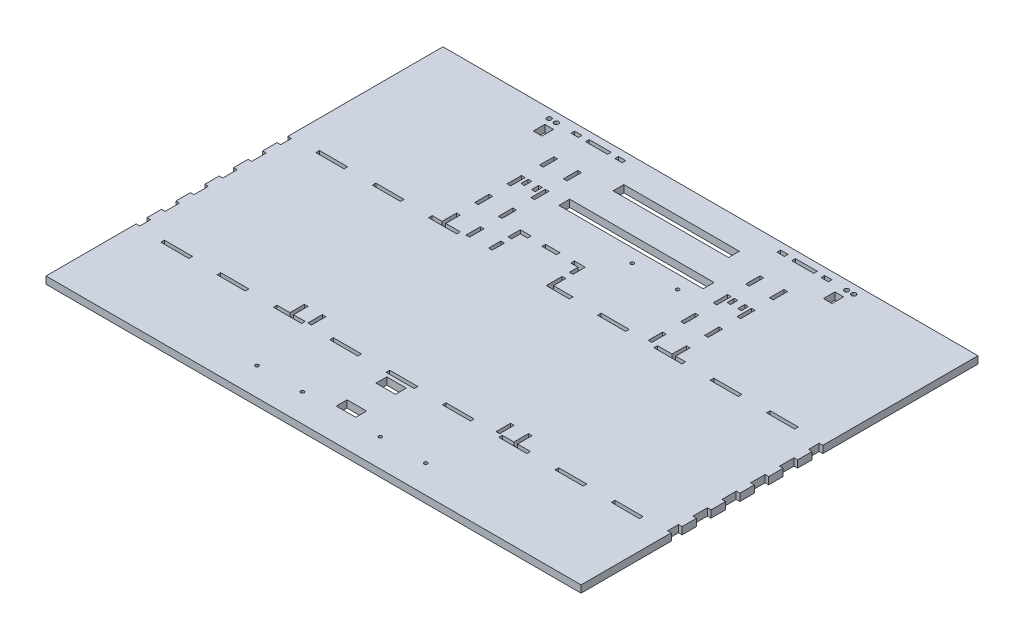
SolidWorks part; units mm, degrees
material "Acrylic (Medium-high impact)"
ref_plane "Front Plane" through (0, 0, 0) normal (0, 0, 1) x (1, 0, 0)
ref_plane "Top Plane" through (0, 0, 0) normal (0, 1, 0) x (1, 0, 0)
ref_plane "Right Plane" through (0, 0, 0) normal (1, 0, 0) x (0, 0, -1)
sketch "Sketch1" plane through (0, 0, 0) normal (0, 1, 0) x (1, 0, 0)
  line L1 (-235.3945, 69.85) -> (235.3945, 69.85)
  line L2 (-235.3945, 69.85) -> (-235.3945, -69.85)
  line L3 (-235.3945, -69.85) -> (235.3945, -69.85)
  line L4 (235.3945, 69.85) -> (235.3945, -69.85)
  point P4 (-235.3945, 0)
  point P6 (0, 69.85)
  dimension "D1" = 139.7
  dimension "D2" = 470.789
extrude "Boss-Extrude1" add sketch "Sketch1" along normal blind 6.35
sketch "Sketch2" plane through (0, 6.35, 0) normal (0, 1, 0) x (1, 0, 0)
  line L0 (235.3945, -69.85) -> (235.3945, 69.85) construction
  line L1 (-235.3945, 69.85) -> (235.3945, 69.85)
  line L2 (-235.3945, 69.85) -> (-235.3945, -69.85)
  line L3 (-235.3945, -69.85) -> (235.3945, -69.85)
  line L4 (235.3945, 69.85) -> (235.3945, -69.85)
  line L5 (-235.3945, -69.85) -> (235.3945, -69.85) construction
  line L7 (-232.2195, 66.675) -> (232.2195, 66.675)
  line L8 (-232.2195, 66.675) -> (-232.2195, -66.675)
  line L9 (-232.2195, -66.675) -> (232.2195, -66.675)
  line L10 (232.2195, 66.675) -> (232.2195, -66.675)
  point P7 (-232.2195, 0)
  point P14 (-235.3945, 0)
  point P15 (0, -66.675)
  point P16 (0, -69.85)
  point P17 (232.2195, 0)
  point P18 (235.3945, 0)
  dimension "D1" = 3.175
  dimension "D2" = 3.175
extrude "Boss-Extrude2" add sketch "Sketch2" along normal blind 298.45
sketch "Sketch3" plane through (0, 0, 69.85) normal (0, 0, 1) x (1, 0, 0)
  line L0 (73.4695, 304.8) -> (73.4695, 0) construction
  line L2 (-232.2195, 6.35) -> (232.2195, 6.35) construction
  line L4 (70.1675, 292.354) -> (70.1675, 6.35)
  line L5 (70.1675, 6.35) -> (76.7715, 6.35)
  line L6 (76.7715, 283.2407) -> (76.7715, 6.35)
  line L11 (76.7715, 101.6) -> (63.0555, 101.6) construction
  line L12 (-235.3945, 0) -> (235.3945, 0) construction
  line L13 (60.2615, 88.9) -> (60.2615, 101.6) construction
  line L14 (57.4675, 88.9) -> (63.0555, 88.9)
  line L15 (57.4675, 88.9) -> (57.4675, 71.9667)
  line L16 (57.4675, 71.9667) -> (63.0555, 71.9667)
  line L17 (63.0555, 88.9) -> (63.0555, 71.9667)
  line L18 (57.4675, 42.3333) -> (63.0555, 42.3333)
  line L19 (57.4675, 42.3333) -> (57.4675, 59.2667)
  line L20 (57.4675, 59.2667) -> (63.0555, 59.2667)
  line L21 (63.0555, 42.3333) -> (63.0555, 59.2667)
  line L26 (57.4675, 29.6333) -> (63.0555, 29.6333)
  line L27 (57.4675, 29.6333) -> (57.4675, 12.7)
  line L28 (57.4675, 12.7) -> (63.0555, 12.7)
  line L29 (63.0555, 29.6333) -> (63.0555, 12.7)
  line L30 (60.2615, 59.2667) -> (60.2615, 71.9667) construction
  line L31 (60.2615, 29.6333) -> (60.2615, 42.3333) construction
  line L32 (60.2615, 12.7) -> (60.2615, 0) construction
  line L33 (-235.3945, 304.8) -> (235.3945, 304.8) construction
  line L34 (-76.7715, 283.2407) -> (-76.7715, 6.35)
  line L35 (-76.7715, 6.35) -> (-70.1675, 6.35)
  line L36 (-70.1675, 292.354) -> (-70.1675, 6.35)
  line L37 (-70.1675, 292.354) -> (-89.7255, 292.354)
  line L38 (-79.3115, 285.7807) -> (-89.7255, 285.7807)
  line L39 (-89.7255, 292.354) -> (-89.7255, 285.7807)
  line L40 (-70.1675, 101.6) -> (-57.4675, 101.6) construction
  line L41 (-60.2615, 88.9) -> (-60.2615, 101.6) construction
  line L42 (-63.0555, 88.9) -> (-57.4675, 88.9)
  line L43 (-63.0555, 88.9) -> (-63.0555, 71.9667)
  line L44 (-63.0555, 71.9667) -> (-57.4675, 71.9667)
  line L45 (-57.4675, 88.9) -> (-57.4675, 71.9667)
  line L46 (-63.0555, 42.3333) -> (-57.4675, 42.3333)
  line L47 (-63.0555, 42.3333) -> (-63.0555, 59.2667)
  line L48 (-63.0555, 59.2667) -> (-57.4675, 59.2667)
  line L49 (-57.4675, 42.3333) -> (-57.4675, 59.2667)
  line L50 (-63.0555, 29.6333) -> (-57.4675, 29.6333)
  line L51 (-63.0555, 29.6333) -> (-63.0555, 12.7)
  line L52 (-63.0555, 12.7) -> (-57.4675, 12.7)
  line L53 (-57.4675, 29.6333) -> (-57.4675, 12.7)
  line L54 (-60.2615, 59.2667) -> (-60.2615, 71.9667) construction
  line L55 (-60.2615, 29.6333) -> (-60.2615, 42.3333) construction
  line L56 (-60.2615, 12.7) -> (-60.2615, 0) construction
  line L58 (70.1675, 292.354) -> (89.7255, 292.354)
  line L59 (89.7255, 292.354) -> (89.7255, 285.7807)
  line L60 (79.3115, 285.7807) -> (89.7255, 285.7807)
  line L61 (-235.3945, 304.8) -> (-235.3945, 0) construction
  line L62 (235.3945, 304.8) -> (235.3945, 0) construction
  arc A1 (-76.7715, 283.2407) -> (-79.3115, 285.7807) centre (-79.3115, 283.2407) ccw
  arc A2 (79.3115, 285.7807) -> (76.7715, 283.2407) centre (79.3115, 283.2407) ccw
  point P5 (73.4695, 6.35)
  dimension "D14" = 2.54
  dimension "D1" = 6.604
  dimension "D2" = 6.5733
  dimension "D3" = 158.623
  dimension "D4" = 158.623
  dimension "D6" = 101.6
  dimension "D7" = 12.7
  dimension "D8" = 12.7
  dimension "D9" = 5.588
  dimension "D11" = 6.604
  dimension "D12" = 12.954
  dimension "D13" = 286.004
  dimension "D15" = 12.7
  dimension "D16" = 12.7
  dimension "D17" = 5.588
extrude "Door Slot" cut sketch "Sketch3" against normal blind 12.7
sketch "Sketch4" plane through (0, 0, -66.675) normal (0, 0, 1) x (1, 0, 0)
  line L0 (-235.3945, 304.8) -> (235.3945, 304.8) construction
  line L1 (63.8175, 304.8) -> (70.1675, 304.8)
  line L2 (63.8175, 304.8) -> (63.8175, 6.35)
  line L3 (63.8175, 6.35) -> (70.1675, 6.35)
  line L4 (70.1675, 304.8) -> (70.1675, 6.35)
  line L5 (92.9005, 263.525) -> (92.9005, 247.65) construction
  line L7 (89.7255, 304.8) -> (96.0755, 304.8)
  line L8 (89.7255, 304.8) -> (89.7255, 6.35)
  line L9 (89.7255, 6.35) -> (96.0755, 6.35)
  line L10 (96.0755, 304.8) -> (96.0755, 6.35)
  line L11 (232.2195, 6.35) -> (-232.2195, 6.35) construction
  line L13 (70.1675, 304.8) -> (63.8175, 304.8)
  line L14 (70.1675, 304.8) -> (70.1675, 292.1)
  line L15 (70.1675, 292.1) -> (63.8175, 292.1)
  line L16 (63.8175, 304.8) -> (63.8175, 292.1)
  line L17 (70.1675, 276.225) -> (63.8175, 276.225)
  line L18 (70.1675, 276.225) -> (70.1675, 263.525)
  line L19 (70.1675, 263.525) -> (63.8175, 263.525)
  line L20 (63.8175, 276.225) -> (63.8175, 263.525)
  line L21 (63.8175, 6.35) -> (70.1675, 6.35)
  line L22 (63.8175, 6.35) -> (63.8175, 19.05)
  line L23 (63.8175, 19.05) -> (70.1675, 19.05)
  line L24 (70.1675, 6.35) -> (70.1675, 19.05)
  line L25 (63.8175, 34.925) -> (70.1675, 34.925)
  line L26 (63.8175, 34.925) -> (63.8175, 47.625)
  line L27 (63.8175, 47.625) -> (70.1675, 47.625)
  line L28 (70.1675, 34.925) -> (70.1675, 47.625)
  line L29 (63.8175, 92.075) -> (70.1675, 92.075)
  line L30 (63.8175, 92.075) -> (63.8175, 104.775)
  line L31 (63.8175, 104.775) -> (70.1675, 104.775)
  line L32 (70.1675, 92.075) -> (70.1675, 104.775)
  line L33 (63.8175, 149.225) -> (70.1675, 149.225)
  line L34 (63.8175, 149.225) -> (63.8175, 161.925)
  line L35 (63.8175, 161.925) -> (70.1675, 161.925)
  line L36 (70.1675, 149.225) -> (70.1675, 161.925)
  line L37 (63.8175, 177.8) -> (70.1675, 177.8)
  line L38 (63.8175, 177.8) -> (63.8175, 190.5)
  line L39 (63.8175, 190.5) -> (70.1675, 190.5)
  line L40 (70.1675, 177.8) -> (70.1675, 190.5)
  line L41 (63.8175, 206.375) -> (70.1675, 206.375)
  line L42 (63.8175, 206.375) -> (63.8175, 219.075)
  line L43 (63.8175, 219.075) -> (70.1675, 219.075)
  line L44 (70.1675, 206.375) -> (70.1675, 219.075)
  line L45 (63.8175, 234.95) -> (70.1675, 234.95)
  line L46 (63.8175, 234.95) -> (63.8175, 247.65)
  line L47 (63.8175, 247.65) -> (70.1675, 247.65)
  line L48 (70.1675, 234.95) -> (70.1675, 247.65)
  line L49 (70.1675, 133.35) -> (63.8175, 133.35)
  line L50 (70.1675, 133.35) -> (70.1675, 120.65)
  line L51 (70.1675, 120.65) -> (63.8175, 120.65)
  line L52 (63.8175, 133.35) -> (63.8175, 120.65)
  line L53 (70.1675, 76.2) -> (63.8175, 76.2)
  line L54 (70.1675, 76.2) -> (70.1675, 63.5)
  line L55 (70.1675, 63.5) -> (63.8175, 63.5)
  line L56 (63.8175, 76.2) -> (63.8175, 63.5)
  line L57 (66.9925, 304.8) -> (66.9925, 292.1) construction
  line L58 (66.9925, 292.1) -> (66.9925, 276.225) construction
  line L59 (66.9925, 276.225) -> (66.9925, 263.525) construction
  line L60 (66.9925, 247.65) -> (66.9925, 234.95) construction
  line L61 (66.9925, 234.95) -> (66.9925, 219.075) construction
  line L62 (66.9925, 219.075) -> (66.9925, 206.375) construction
  line L63 (66.9925, 206.375) -> (66.9925, 190.5) construction
  line L64 (66.9925, 190.5) -> (66.9925, 177.8) construction
  line L65 (66.9925, 177.8) -> (66.9925, 161.925) construction
  line L66 (66.9925, 161.925) -> (66.9925, 149.225) construction
  line L67 (66.9925, 133.35) -> (66.9925, 120.65) construction
  line L68 (66.9925, 120.65) -> (66.9925, 104.775) construction
  line L69 (66.9925, 104.775) -> (66.9925, 92.075) construction
  line L70 (66.9925, 92.075) -> (66.9925, 76.2) construction
  line L71 (66.9925, 76.2) -> (66.9925, 63.5) construction
  line L72 (66.9925, 63.5) -> (66.9925, 47.625) construction
  line L73 (66.9925, 47.625) -> (66.9925, 34.925) construction
  line L74 (66.9925, 34.925) -> (66.9925, 19.05) construction
  line L75 (66.9925, 19.05) -> (66.9925, 6.35) construction
  line L76 (66.9925, 149.225) -> (66.9925, 133.35) construction
  line L77 (66.9925, 263.525) -> (66.9925, 247.65) construction
  line L78 (79.9465, 304.8) -> (79.9465, 0) construction
  line L79 (235.3945, 304.8) -> (-235.3945, 304.8) construction
  line L80 (235.3945, 0) -> (-235.3945, 0) construction
  line L81 (79.9465, 15.1854) -> (89.7255, 15.1854) construction
  line L82 (79.9465, 15.1854) -> (70.1675, 15.1854) construction
  line L83 (92.9005, 149.225) -> (92.9005, 133.35) construction
  line L84 (92.9005, 19.05) -> (92.9005, 6.35) construction
  line L85 (92.9005, 34.925) -> (92.9005, 19.05) construction
  line L86 (92.9005, 47.625) -> (92.9005, 34.925) construction
  line L87 (92.9005, 63.5) -> (92.9005, 47.625) construction
  line L88 (92.9005, 76.2) -> (92.9005, 63.5) construction
  line L89 (92.9005, 92.075) -> (92.9005, 76.2) construction
  line L90 (92.9005, 104.775) -> (92.9005, 92.075) construction
  line L91 (92.9005, 120.65) -> (92.9005, 104.775) construction
  line L92 (92.9005, 133.35) -> (92.9005, 120.65) construction
  line L93 (92.9005, 161.925) -> (92.9005, 149.225) construction
  line L94 (92.9005, 177.8) -> (92.9005, 161.925) construction
  line L95 (92.9005, 190.5) -> (92.9005, 177.8) construction
  line L96 (92.9005, 206.375) -> (92.9005, 190.5) construction
  line L97 (92.9005, 219.075) -> (92.9005, 206.375) construction
  line L98 (92.9005, 234.95) -> (92.9005, 219.075) construction
  line L99 (92.9005, 247.65) -> (92.9005, 234.95) construction
  line L100 (92.9005, 276.225) -> (92.9005, 263.525) construction
  line L101 (92.9005, 292.1) -> (92.9005, 276.225) construction
  line L102 (92.9005, 304.8) -> (92.9005, 292.1) construction
  line L103 (96.0755, 76.2) -> (96.0755, 63.5)
  line L104 (89.7255, 63.5) -> (96.0755, 63.5)
  line L105 (89.7255, 76.2) -> (89.7255, 63.5)
  line L106 (89.7255, 76.2) -> (96.0755, 76.2)
  line L107 (96.0755, 133.35) -> (96.0755, 120.65)
  line L108 (89.7255, 120.65) -> (96.0755, 120.65)
  line L109 (89.7255, 133.35) -> (89.7255, 120.65)
  line L110 (89.7255, 133.35) -> (96.0755, 133.35)
  line L111 (89.7255, 234.95) -> (89.7255, 247.65)
  line L112 (96.0755, 247.65) -> (89.7255, 247.65)
  line L113 (96.0755, 234.95) -> (96.0755, 247.65)
  line L114 (96.0755, 234.95) -> (89.7255, 234.95)
  line L115 (89.7255, 206.375) -> (89.7255, 219.075)
  line L116 (96.0755, 219.075) -> (89.7255, 219.075)
  line L117 (96.0755, 206.375) -> (96.0755, 219.075)
  line L118 (96.0755, 206.375) -> (89.7255, 206.375)
  line L119 (89.7255, 177.8) -> (89.7255, 190.5)
  line L120 (96.0755, 190.5) -> (89.7255, 190.5)
  line L121 (96.0755, 177.8) -> (96.0755, 190.5)
  line L122 (96.0755, 177.8) -> (89.7255, 177.8)
  line L123 (89.7255, 149.225) -> (89.7255, 161.925)
  line L124 (96.0755, 161.925) -> (89.7255, 161.925)
  line L125 (96.0755, 149.225) -> (96.0755, 161.925)
  line L126 (96.0755, 149.225) -> (89.7255, 149.225)
  line L127 (89.7255, 92.075) -> (89.7255, 104.775)
  line L128 (96.0755, 104.775) -> (89.7255, 104.775)
  line L129 (96.0755, 92.075) -> (96.0755, 104.775)
  line L130 (96.0755, 92.075) -> (89.7255, 92.075)
  line L131 (89.7255, 34.925) -> (89.7255, 47.625)
  line L132 (96.0755, 47.625) -> (89.7255, 47.625)
  line L133 (96.0755, 34.925) -> (96.0755, 47.625)
  line L134 (96.0755, 34.925) -> (89.7255, 34.925)
  line L135 (89.7255, 6.35) -> (89.7255, 19.05)
  line L136 (96.0755, 19.05) -> (89.7255, 19.05)
  line L137 (96.0755, 6.35) -> (96.0755, 19.05)
  line L138 (96.0755, 6.35) -> (89.7255, 6.35)
  line L139 (96.0755, 276.225) -> (96.0755, 263.525)
  line L140 (89.7255, 263.525) -> (96.0755, 263.525)
  line L141 (89.7255, 276.225) -> (89.7255, 263.525)
  line L142 (89.7255, 276.225) -> (96.0755, 276.225)
  line L143 (96.0755, 304.8) -> (96.0755, 292.1)
  line L144 (89.7255, 292.1) -> (96.0755, 292.1)
  line L145 (89.7255, 304.8) -> (89.7255, 292.1)
  line L146 (89.7255, 304.8) -> (96.0755, 304.8)
  line L147 (89.7255, 304.8) -> (89.7255, 6.35)
  line L148 (96.0755, 6.35) -> (89.7255, 6.35)
  line L149 (96.0755, 304.8) -> (96.0755, 6.35)
  line L150 (96.0755, 304.8) -> (89.7255, 304.8)
  line L151 (-96.0755, 304.8) -> (-89.7255, 304.8)
  line L152 (-96.0755, 304.8) -> (-96.0755, 6.35)
  line L153 (-96.0755, 6.35) -> (-89.7255, 6.35)
  line L154 (-89.7255, 304.8) -> (-89.7255, 6.35)
  line L155 (-66.9925, 263.525) -> (-66.9925, 247.65) construction
  line L156 (-70.1675, 304.8) -> (-63.8175, 304.8)
  line L157 (-70.1675, 304.8) -> (-70.1675, 6.35)
  line L158 (-70.1675, 6.35) -> (-63.8175, 6.35)
  line L159 (-63.8175, 304.8) -> (-63.8175, 6.35)
  line L160 (-89.7255, 304.8) -> (-96.0755, 304.8)
  line L161 (-89.7255, 304.8) -> (-89.7255, 292.1)
  line L162 (-89.7255, 292.1) -> (-96.0755, 292.1)
  line L163 (-96.0755, 304.8) -> (-96.0755, 292.1)
  line L164 (-89.7255, 276.225) -> (-96.0755, 276.225)
  line L165 (-89.7255, 276.225) -> (-89.7255, 263.525)
  line L166 (-89.7255, 263.525) -> (-96.0755, 263.525)
  line L167 (-96.0755, 276.225) -> (-96.0755, 263.525)
  line L168 (-96.0755, 6.35) -> (-89.7255, 6.35)
  line L169 (-96.0755, 6.35) -> (-96.0755, 19.05)
  line L170 (-96.0755, 19.05) -> (-89.7255, 19.05)
  line L171 (-89.7255, 6.35) -> (-89.7255, 19.05)
  line L172 (-96.0755, 34.925) -> (-89.7255, 34.925)
  line L173 (-96.0755, 34.925) -> (-96.0755, 47.625)
  line L174 (-96.0755, 47.625) -> (-89.7255, 47.625)
  line L175 (-89.7255, 34.925) -> (-89.7255, 47.625)
  line L176 (-96.0755, 92.075) -> (-89.7255, 92.075)
  line L177 (-96.0755, 92.075) -> (-96.0755, 104.775)
  line L178 (-96.0755, 104.775) -> (-89.7255, 104.775)
  line L179 (-89.7255, 92.075) -> (-89.7255, 104.775)
  line L180 (-96.0755, 149.225) -> (-89.7255, 149.225)
  line L181 (-96.0755, 149.225) -> (-96.0755, 161.925)
  line L182 (-96.0755, 161.925) -> (-89.7255, 161.925)
  line L183 (-89.7255, 149.225) -> (-89.7255, 161.925)
  line L184 (-96.0755, 177.8) -> (-89.7255, 177.8)
  line L185 (-96.0755, 177.8) -> (-96.0755, 190.5)
  line L186 (-96.0755, 190.5) -> (-89.7255, 190.5)
  line L187 (-89.7255, 177.8) -> (-89.7255, 190.5)
  line L188 (-96.0755, 206.375) -> (-89.7255, 206.375)
  line L189 (-96.0755, 206.375) -> (-96.0755, 219.075)
  line L190 (-96.0755, 219.075) -> (-89.7255, 219.075)
  line L191 (-89.7255, 206.375) -> (-89.7255, 219.075)
  line L192 (-96.0755, 234.95) -> (-89.7255, 234.95)
  line L193 (-96.0755, 234.95) -> (-96.0755, 247.65)
  line L194 (-96.0755, 247.65) -> (-89.7255, 247.65)
  line L195 (-89.7255, 234.95) -> (-89.7255, 247.65)
  line L196 (-89.7255, 133.35) -> (-96.0755, 133.35)
  line L197 (-89.7255, 133.35) -> (-89.7255, 120.65)
  line L198 (-89.7255, 120.65) -> (-96.0755, 120.65)
  line L199 (-96.0755, 133.35) -> (-96.0755, 120.65)
  line L200 (-89.7255, 76.2) -> (-96.0755, 76.2)
  line L201 (-89.7255, 76.2) -> (-89.7255, 63.5)
  line L202 (-89.7255, 63.5) -> (-96.0755, 63.5)
  line L203 (-96.0755, 76.2) -> (-96.0755, 63.5)
  line L204 (-92.9005, 304.8) -> (-92.9005, 292.1) construction
  line L205 (-92.9005, 292.1) -> (-92.9005, 276.225) construction
  line L206 (-92.9005, 276.225) -> (-92.9005, 263.525) construction
  line L207 (-92.9005, 247.65) -> (-92.9005, 234.95) construction
  line L208 (-92.9005, 234.95) -> (-92.9005, 219.075) construction
  line L209 (-92.9005, 219.075) -> (-92.9005, 206.375) construction
  line L210 (-92.9005, 206.375) -> (-92.9005, 190.5) construction
  line L211 (-92.9005, 190.5) -> (-92.9005, 177.8) construction
  line L212 (-92.9005, 177.8) -> (-92.9005, 161.925) construction
  line L213 (-92.9005, 161.925) -> (-92.9005, 149.225) construction
  line L214 (-92.9005, 133.35) -> (-92.9005, 120.65) construction
  line L215 (-92.9005, 120.65) -> (-92.9005, 104.775) construction
  line L216 (-92.9005, 104.775) -> (-92.9005, 92.075) construction
  line L217 (-92.9005, 92.075) -> (-92.9005, 76.2) construction
  line L218 (-92.9005, 76.2) -> (-92.9005, 63.5) construction
  line L219 (-92.9005, 63.5) -> (-92.9005, 47.625) construction
  line L220 (-92.9005, 47.625) -> (-92.9005, 34.925) construction
  line L221 (-92.9005, 34.925) -> (-92.9005, 19.05) construction
  line L222 (-92.9005, 19.05) -> (-92.9005, 6.35) construction
  line L223 (-92.9005, 149.225) -> (-92.9005, 133.35) construction
  line L224 (-92.9005, 263.525) -> (-92.9005, 247.65) construction
  line L225 (-79.9465, 304.8) -> (-79.9465, 0) construction
  line L226 (-79.9465, 341.727) -> (-70.1675, 341.727) construction
  line L227 (-79.9465, 341.727) -> (-89.7255, 341.727) construction
  line L228 (-66.9925, 149.225) -> (-66.9925, 133.35) construction
  line L229 (-66.9925, 19.05) -> (-66.9925, 6.35) construction
  line L230 (-66.9925, 34.925) -> (-66.9925, 19.05) construction
  line L231 (-66.9925, 47.625) -> (-66.9925, 34.925) construction
  line L232 (-66.9925, 63.5) -> (-66.9925, 47.625) construction
  line L233 (-66.9925, 76.2) -> (-66.9925, 63.5) construction
  line L234 (-66.9925, 92.075) -> (-66.9925, 76.2) construction
  line L235 (-66.9925, 104.775) -> (-66.9925, 92.075) construction
  line L236 (-66.9925, 120.65) -> (-66.9925, 104.775) construction
  line L237 (-66.9925, 133.35) -> (-66.9925, 120.65) construction
  line L238 (-66.9925, 161.925) -> (-66.9925, 149.225) construction
  line L239 (-66.9925, 177.8) -> (-66.9925, 161.925) construction
  line L240 (-66.9925, 190.5) -> (-66.9925, 177.8) construction
  line L241 (-66.9925, 206.375) -> (-66.9925, 190.5) construction
  line L242 (-66.9925, 219.075) -> (-66.9925, 206.375) construction
  line L243 (-66.9925, 234.95) -> (-66.9925, 219.075) construction
  line L244 (-66.9925, 247.65) -> (-66.9925, 234.95) construction
  line L245 (-66.9925, 276.225) -> (-66.9925, 263.525) construction
  line L246 (-66.9925, 292.1) -> (-66.9925, 276.225) construction
  line L247 (-66.9925, 304.8) -> (-66.9925, 292.1) construction
  line L248 (-63.8175, 76.2) -> (-63.8175, 63.5)
  line L249 (-70.1675, 63.5) -> (-63.8175, 63.5)
  line L250 (-70.1675, 76.2) -> (-70.1675, 63.5)
  line L251 (-70.1675, 76.2) -> (-63.8175, 76.2)
  line L252 (-63.8175, 133.35) -> (-63.8175, 120.65)
  line L253 (-70.1675, 120.65) -> (-63.8175, 120.65)
  line L254 (-70.1675, 133.35) -> (-70.1675, 120.65)
  line L255 (-70.1675, 133.35) -> (-63.8175, 133.35)
  line L256 (-70.1675, 234.95) -> (-70.1675, 247.65)
  line L257 (-63.8175, 247.65) -> (-70.1675, 247.65)
  line L258 (-63.8175, 234.95) -> (-63.8175, 247.65)
  line L259 (-63.8175, 234.95) -> (-70.1675, 234.95)
  line L260 (-70.1675, 206.375) -> (-70.1675, 219.075)
  line L261 (-63.8175, 219.075) -> (-70.1675, 219.075)
  line L262 (-63.8175, 206.375) -> (-63.8175, 219.075)
  line L263 (-63.8175, 206.375) -> (-70.1675, 206.375)
  line L264 (-70.1675, 177.8) -> (-70.1675, 190.5)
  line L265 (-63.8175, 190.5) -> (-70.1675, 190.5)
  line L266 (-63.8175, 177.8) -> (-63.8175, 190.5)
  line L267 (-63.8175, 177.8) -> (-70.1675, 177.8)
  line L268 (-70.1675, 149.225) -> (-70.1675, 161.925)
  line L269 (-63.8175, 161.925) -> (-70.1675, 161.925)
  line L270 (-63.8175, 149.225) -> (-63.8175, 161.925)
  line L271 (-63.8175, 149.225) -> (-70.1675, 149.225)
  line L272 (-70.1675, 92.075) -> (-70.1675, 104.775)
  line L273 (-63.8175, 104.775) -> (-70.1675, 104.775)
  line L274 (-63.8175, 92.075) -> (-63.8175, 104.775)
  line L275 (-63.8175, 92.075) -> (-70.1675, 92.075)
  line L276 (-70.1675, 34.925) -> (-70.1675, 47.625)
  line L277 (-63.8175, 47.625) -> (-70.1675, 47.625)
  line L278 (-63.8175, 34.925) -> (-63.8175, 47.625)
  line L279 (-63.8175, 34.925) -> (-70.1675, 34.925)
  line L280 (-70.1675, 6.35) -> (-70.1675, 19.05)
  line L281 (-63.8175, 19.05) -> (-70.1675, 19.05)
  line L282 (-63.8175, 6.35) -> (-63.8175, 19.05)
  line L283 (-63.8175, 6.35) -> (-70.1675, 6.35)
  line L284 (-63.8175, 276.225) -> (-63.8175, 263.525)
  line L285 (-70.1675, 263.525) -> (-63.8175, 263.525)
  line L286 (-70.1675, 276.225) -> (-70.1675, 263.525)
  line L287 (-70.1675, 276.225) -> (-63.8175, 276.225)
  line L288 (-63.8175, 304.8) -> (-63.8175, 292.1)
  line L289 (-70.1675, 292.1) -> (-63.8175, 292.1)
  line L290 (-70.1675, 304.8) -> (-70.1675, 292.1)
  line L291 (-70.1675, 304.8) -> (-63.8175, 304.8)
  line L292 (-70.1675, 304.8) -> (-70.1675, 6.35)
  line L293 (-63.8175, 6.35) -> (-70.1675, 6.35)
  line L294 (-63.8175, 304.8) -> (-63.8175, 6.35)
  line L295 (-63.8175, 304.8) -> (-70.1675, 304.8)
  line L296 (-235.3945, 0) -> (235.3945, 0) construction
  line L297 (-89.7255, 292.354) -> (-89.7255, 285.7807) construction
  line L298 (-70.1675, 6.35) -> (-70.1675, 292.354) construction
  line L299 (70.1675, 292.354) -> (70.1675, 6.35) construction
  line L300 (89.7255, 285.7807) -> (89.7255, 292.354) construction
  dimension "D1" = 6.35
  dimension "D2" = 12.7
  dimension "D3" = 6.35
  dimension "D4" = 12.7
extrude "Door Guide Holes" cut sketch "Sketch4" against normal up to next (3.175 mm away) contours L2 L47 L4 L19 | L45 L2 L43 L4 | L41 L2 L39 L4 | L37 L2 L35 L4 | L49 L4 L33 L2 | L4 L51 L2 L31 | L53 L4 L29 L2 | L4 L55 L2 L27 | L25 L2 L23 L4 | L164 L154 L162 L152 | L152 L194 L154 L166 | L192 L152 L190 L154 | L188 L152 L186 L154 | L184 L152 L182 L154 | L196 L154 L180 L152 | L154 L198 L152 L178 | L200 L154 L176 L152 | L154 L202 L152 L174 | L172 L152 L170 L154 | L144 L8 L142 L10 | L140 L8 L112 L10 | L116 L10 L114 L8 | L120 L10 L118 L8 | L124 L10 L122 L8 | L10 L126 L8 L110 | L128 L10 L108 L8 | L10 L130 L8 L106 | L132 L10 L104 L8 | L136 L10 L134 L8 | L289 L157 L287 L159 | L285 L157 L257 L159 | L261 L159 L259 L157 | L265 L159 L263 L157 | L269 L159 L267 L157 | L159 L271 L157 L255 | L273 L159 L253 L157 | L159 L275 L157 L251 | L277 L159 L249 L157 | L281 L159 L279 L157 | L17 L4 L15 L2 region at (66.9925, 284.1625, -66.675) region at (66.9925, 255.5875, -66.675) region at (66.9925, 227.0125, -66.675) region at (66.9925, 198.4375, -66.675) region at (66.9925, 169.8625, -66.675) region at (66.9925, 141.2875, -66.675) region at (66.9925, 112.7125, -66.675) region at (66.9925, 84.1375, -66.675) region at (66.9925, 55.5625, -66.675) region at (66.9925, 26.9875, -66.675) region at (92.9005, 284.1625, -66.675) region at (92.9005, 255.5875, -66.675) region at (92.9005, 227.0125, -66.675) region at (92.9005, 198.4375, -66.675) region at (92.9005, 169.8625, -66.675) region at (92.9005, 141.2875, -66.675) region at (92.9005, 112.7125, -66.675) region at (92.9005, 84.1375, -66.675) region at (92.9005, 55.5625, -66.675) region at (92.9005, 26.9875, -66.675) region at (-92.9005, 284.1625, -66.675) region at (-92.9005, 255.5875, -66.675) region at (-92.9005, 227.0125, -66.675) region at (-92.9005, 198.4375, -66.675) region at (-92.9005, 169.8625, -66.675) region at (-92.9005, 141.2875, -66.675) region at (-92.9005, 112.7125, -66.675) region at (-92.9005, 84.1375, -66.675) region at (-92.9005, 55.5625, -66.675) region at (-92.9005, 26.9875, -66.675) region at (-66.9925, 284.1625, -66.675) region at (-66.9925, 255.5875, -66.675) region at (-66.9925, 227.0125, -66.675) region at (-66.9925, 198.4375, -66.675) region at (-66.9925, 169.8625, -66.675) region at (-66.9925, 141.2875, -66.675) region at (-66.9925, 112.7125, -66.675) region at (-66.9925, 84.1375, -66.675) region at (-66.9925, 55.5625, -66.675) region at (-66.9925, 26.9875, -66.675)
sketch "Lever Holes" plane through (0, 0, -69.85) normal (0, 0, 1) x (1, 0, 0)
  line L0 (-53.2675, 37.685) -> (-27.8675, 37.685)
  line L1 (-53.2675, 37.685) -> (-53.2675, 30.065)
  line L2 (-53.2675, 30.065) -> (-27.8675, 30.065)
  line L3 (-27.8675, 37.685) -> (-27.8675, 30.065)
  line L4 (-53.8175, 16.35) -> (-49.8175, 16.35)
  line L5 (-53.8175, 16.35) -> (-53.8175, 10)
  line L6 (-53.8175, 10) -> (-49.8175, 10)
  line L7 (-49.8175, 16.35) -> (-49.8175, 10)
  line L8 (-7.8175, 16.35) -> (-3.8175, 16.35)
  line L9 (-7.8175, 16.35) -> (-7.8175, 10)
  line L10 (-7.8175, 10) -> (-3.8175, 10)
  line L11 (-3.8175, 16.35) -> (-3.8175, 10)
  line L12 (-49.8175, 13.175) -> (-7.8175, 13.175) construction
  line L13 (76.7715, 6.35) -> (76.7715, 283.2407) construction
  line L14 (76.7715, 6.35) -> (232.2195, 6.35) construction
  line L15 (232.2195, 6.35) -> (-232.2195, 6.35) construction
  line L16 (216.3445, 160.275) -> (216.3445, 144.525) construction
  line L17 (235.3945, 304.8) -> (235.3945, 0) construction
  line L18 (0, -3.4925) -> (0, 3.4925) construction
  line L19 (76.7715, 154.6735) -> (-76.7715, 154.6735) construction
  line L20 (-76.7715, 283.2407) -> (-76.7715, 6.35) construction
  line L21 (0, 171.6172) -> (0, 142.0428) construction
  line L22 (7.8175, 16.35) -> (7.8175, 10)
  line L23 (7.8175, 10) -> (3.8175, 10)
  line L24 (3.8175, 16.35) -> (3.8175, 10)
  line L25 (7.8175, 16.35) -> (3.8175, 16.35)
  line L26 (53.2675, 37.685) -> (53.2675, 30.065)
  line L27 (53.2675, 30.065) -> (27.8675, 30.065)
  line L28 (27.8675, 37.685) -> (27.8675, 30.065)
  line L29 (53.2675, 37.685) -> (27.8675, 37.685)
  line L30 (53.8175, 16.35) -> (53.8175, 10)
  line L31 (53.8175, 10) -> (49.8175, 10)
  line L32 (49.8175, 16.35) -> (49.8175, 10)
  line L33 (53.8175, 16.35) -> (49.8175, 16.35)
  line L35 (63.8175, 19.05) -> (63.8175, 34.925) construction
  circle A0 centre (216.3445, 160.275) radius 1.5
  circle A1 centre (216.3445, 144.525) radius 1.5
  circle A2 centre (-216.3445, 160.275) radius 1.5
  circle A3 centre (-216.3445, 144.525) radius 1.5
  point P13 (-40.5675, 30.065)
  point P31 (216.3445, 152.4)
  point P32 (235.3945, 152.4)
  dimension "D10" = 3
  dimension "D1" = 25.4
  dimension "D2" = 7.62
  dimension "D3" = 4
  dimension "D4" = 6.35
  dimension "D5" = 42
  dimension "D6" = 31.335
  dimension "D7" = 10
  dimension "D8" = 10
  dimension "D9" = 13.25
  dimension "D11" = 15.75
  dimension "D12" = 19.05
extrude "LeverHole Cut" cut sketch "Lever Holes" along normal up to next
extrude "Lbracket Thru Holes" cut sketch "Lever Holes<2>" along normal through all contours A2 | A3 | A0 | A1 | A2 | A3 | A0 | A1 region at (216.3445, 160.275, -69.85) region at (216.3445, 144.525, -69.85) region at (-216.3445, 160.275, -69.85) region at (-216.3445, 144.525, -69.85)
sketch "Lever Holes<2>" plane through (0, 0, -69.85) normal (0, 0, 1) x (1, 0, 0) same geometry as "Lever Holes"
sketch "Sketch8" plane through (-235.3945, 0, 0) normal (-1, 0, 0) x (0, 0, 1)
  line L0 (-69.85, 0) -> (69.85, 0) construction
  circle A0 centre (0, 19.05) radius 3.175
  point P6 (0, 0)
  dimension "D1" = 6.35
  dimension "D2" = 19.05
extrude "Tether Hole" cut sketch "Sketch8" against normal through all
sketch "Sketch16" plane through (0, 0, 69.85) normal (0, 0, 1) x (1, 0, 0)
  line L0 (-235.3945, 304.8) -> (235.3945, 304.8) construction
  line L1 (57.3405, 304.8) -> (102.5525, 304.8)
  line L2 (57.3405, 304.8) -> (57.3405, 295.529)
  line L3 (57.3405, 295.529) -> (102.5525, 295.529)
  line L4 (102.5525, 304.8) -> (102.5525, 295.529)
  line L6 (47.8155, 295.529) -> (57.3405, 295.529)
  line L8 (57.3405, 295.529) -> (57.3405, 304.8)
  line L9 (57.3405, 304.8) -> (47.8155, 304.8)
  line L10 (47.8155, 295.529) -> (47.8155, 304.8)
  line L11 (102.5525, 295.529) -> (112.0775, 295.529)
  line L12 (102.5525, 295.529) -> (102.5525, 304.8)
  line L13 (102.5525, 304.8) -> (112.0775, 304.8)
  line L14 (112.0775, 295.529) -> (112.0775, 304.8)
  line L15 (89.7255, 292.354) -> (70.1675, 292.354) construction
  line L16 (-102.5525, 304.8) -> (-57.3405, 304.8)
  line L17 (-102.5525, 304.8) -> (-102.5525, 295.529)
  line L18 (-102.5525, 295.529) -> (-57.3405, 295.529)
  line L19 (-57.3405, 304.8) -> (-57.3405, 295.529)
  line L20 (-112.0775, 295.529) -> (-102.5525, 295.529)
  line L21 (-102.5525, 295.529) -> (-102.5525, 304.8)
  line L22 (-102.5525, 304.8) -> (-112.0775, 304.8)
  line L23 (-112.0775, 295.529) -> (-112.0775, 304.8)
  line L24 (-57.3405, 295.529) -> (-47.8155, 295.529)
  line L25 (-57.3405, 295.529) -> (-57.3405, 304.8)
  line L26 (-57.3405, 304.8) -> (-47.8155, 304.8)
  line L27 (-47.8155, 295.529) -> (-47.8155, 304.8)
  line L28 (-70.1675, 292.354) -> (-89.7255, 292.354) construction
  point P15 (79.9465, 292.354)
  point P16 (79.9465, 295.529)
  point P25 (-79.9465, 292.354)
  point P28 (-79.9465, 295.529)
  dimension "D1" = 45.212
  dimension "D2" = 3.175
  dimension "D3" = 9.525
  dimension "D4" = 45.212
  dimension "D5" = 9.525
extrude "Door Guide Roof Slots" cut sketch "Sketch16" against normal up to next contours L10 L6 L2 L9 | L11 L14 L13 L4 | L23 L20 L17 L22 | L24 L27 L26 L19 region at (52.578, 300.1645, 69.85) region at (107.315, 300.1645, 69.85) region at (-107.315, 300.1645, 69.85) region at (-52.578, 300.1645, 69.85)
sketch "Bottom" plane through (0, 0, 0) normal (0, -1, 0) x (1, 0, 0)
  line L0 (-232.2195, 66.675) -> (-112.0775, 66.675) construction
  line L1 (-235.3945, 69.85) -> (-210.6161, 69.85)
  line L2 (-235.3945, 69.85) -> (-235.3945, 66.675)
  line L3 (-235.3945, 66.675) -> (-210.6161, 66.675)
  line L4 (-210.6161, 69.85) -> (-210.6161, 66.675)
  line L5 (-210.6161, 69.85) -> (-185.8378, 69.85)
  line L6 (-210.6161, 69.85) -> (-210.6161, 66.675)
  line L7 (-210.6161, 66.675) -> (-185.8378, 66.675)
  line L8 (-185.8378, 69.85) -> (-185.8378, 66.675)
  line L9 (-185.8378, 69.85) -> (-161.0594, 69.85)
  line L10 (-185.8378, 69.85) -> (-185.8378, 66.675)
  line L11 (-185.8378, 66.675) -> (-161.0594, 66.675)
  line L12 (-161.0594, 69.85) -> (-161.0594, 66.675)
  line L13 (-161.0594, 69.85) -> (-136.281, 69.85)
  line L14 (-161.0594, 69.85) -> (-161.0594, 66.675)
  line L15 (-161.0594, 66.675) -> (-136.281, 66.675)
  line L16 (-136.281, 69.85) -> (-136.281, 66.675)
  line L17 (-235.3945, 69.85) -> (235.3945, 69.85) construction
  line L19 (-136.281, 69.85) -> (-111.5027, 69.85)
  line L20 (-136.281, 69.85) -> (-136.281, 66.675)
  line L21 (-136.281, 66.675) -> (-111.5027, 66.675)
  line L22 (-111.5027, 69.85) -> (-111.5027, 66.675)
  line L23 (-111.5027, 69.85) -> (-86.7243, 69.85)
  line L24 (-111.5027, 69.85) -> (-111.5027, 66.675)
  line L25 (-111.5027, 66.675) -> (-86.7243, 66.675)
  line L26 (-86.7243, 69.85) -> (-86.7243, 66.675)
  line L27 (-86.7243, 69.85) -> (-61.9459, 69.85)
  line L28 (-86.7243, 69.85) -> (-86.7243, 66.675)
  line L29 (-86.7243, 66.675) -> (-61.9459, 66.675)
  line L30 (-61.9459, 69.85) -> (-61.9459, 66.675)
  line L31 (-61.9459, 69.85) -> (-37.1676, 69.85)
  line L32 (-61.9459, 69.85) -> (-61.9459, 66.675)
  line L33 (-61.9459, 66.675) -> (-37.1676, 66.675)
  line L34 (-37.1676, 69.85) -> (-37.1676, 66.675)
  line L36 (-37.1676, 69.85) -> (-12.3892, 69.85)
  line L37 (-37.1676, 69.85) -> (-37.1676, 66.675)
  line L38 (-37.1676, 66.675) -> (-12.3892, 66.675)
  line L39 (-12.3892, 69.85) -> (-12.3892, 66.675)
  line L40 (-12.3892, 69.85) -> (12.3892, 69.85)
  line L41 (-12.3892, 69.85) -> (-12.3892, 66.675)
  line L42 (-12.3892, 66.675) -> (12.3892, 66.675)
  line L43 (12.3892, 69.85) -> (12.3892, 66.675)
  line L44 (12.3892, 69.85) -> (37.1676, 69.85)
  line L45 (12.3892, 69.85) -> (12.3892, 66.675)
  line L46 (12.3892, 66.675) -> (37.1676, 66.675)
  line L47 (37.1676, 69.85) -> (37.1676, 66.675)
  line L48 (37.1676, 69.85) -> (61.9459, 69.85)
  line L49 (37.1676, 69.85) -> (37.1676, 66.675)
  line L50 (37.1676, 66.675) -> (61.9459, 66.675)
  line L51 (61.9459, 69.85) -> (61.9459, 66.675)
  line L52 (61.9459, 69.85) -> (86.7243, 69.85)
  line L53 (61.9459, 69.85) -> (61.9459, 66.675)
  line L54 (61.9459, 66.675) -> (86.7243, 66.675)
  line L55 (86.7243, 69.85) -> (86.7243, 66.675)
  line L56 (86.7243, 69.85) -> (111.5027, 69.85)
  line L57 (86.7243, 69.85) -> (86.7243, 66.675)
  line L58 (86.7243, 66.675) -> (111.5027, 66.675)
  line L59 (111.5027, 69.85) -> (111.5027, 66.675)
  line L60 (111.5027, 69.85) -> (136.281, 69.85)
  line L61 (111.5027, 69.85) -> (111.5027, 66.675)
  line L62 (111.5027, 66.675) -> (136.281, 66.675)
  line L63 (136.281, 69.85) -> (136.281, 66.675)
  line L64 (136.281, 69.85) -> (161.0594, 69.85)
  line L65 (136.281, 69.85) -> (136.281, 66.675)
  line L66 (136.281, 66.675) -> (161.0594, 66.675)
  line L67 (161.0594, 69.85) -> (161.0594, 66.675)
  line L68 (161.0594, 69.85) -> (185.8378, 69.85)
  line L69 (161.0594, 69.85) -> (161.0594, 66.675)
  line L70 (161.0594, 66.675) -> (185.8378, 66.675)
  line L71 (185.8378, 69.85) -> (185.8378, 66.675)
  line L72 (185.8378, 69.85) -> (210.6161, 69.85)
  line L73 (185.8378, 69.85) -> (185.8378, 66.675)
  line L74 (185.8378, 66.675) -> (210.6161, 66.675)
  line L75 (210.6161, 69.85) -> (210.6161, 66.675)
  line L76 (-232.2195, -66.675) -> (-232.2195, 66.675) construction
  line L77 (-235.3945, 69.85) -> (-232.2195, 69.85)
  line L78 (-235.3945, 69.85) -> (-235.3945, 57.15)
  line L79 (-235.3945, 57.15) -> (-232.2195, 57.15)
  line L80 (-232.2195, 69.85) -> (-232.2195, 57.15)
  line L82 (-235.3945, 57.15) -> (-232.2195, 57.15)
  line L83 (-235.3945, 57.15) -> (-235.3945, 44.45)
  line L84 (-235.3945, 44.45) -> (-232.2195, 44.45)
  line L85 (-232.2195, 57.15) -> (-232.2195, 44.45)
  line L86 (-235.3945, 44.45) -> (-232.2195, 44.45)
  line L87 (-235.3945, 44.45) -> (-235.3945, 31.75)
  line L88 (-235.3945, 31.75) -> (-232.2195, 31.75)
  line L89 (-232.2195, 44.45) -> (-232.2195, 31.75)
  line L90 (-235.3945, 31.75) -> (-232.2195, 31.75)
  line L91 (-235.3945, 31.75) -> (-235.3945, 19.05)
  line L92 (-235.3945, 19.05) -> (-232.2195, 19.05)
  line L93 (-232.2195, 31.75) -> (-232.2195, 19.05)
  line L94 (-235.3945, 19.05) -> (-232.2195, 19.05)
  line L95 (-235.3945, 19.05) -> (-235.3945, 6.35)
  line L96 (-235.3945, 6.35) -> (-232.2195, 6.35)
  line L97 (-232.2195, 19.05) -> (-232.2195, 6.35)
  line L98 (-235.3945, 6.35) -> (-232.2195, 6.35)
  line L99 (-235.3945, 6.35) -> (-235.3945, -6.35)
  line L100 (-235.3945, -6.35) -> (-232.2195, -6.35)
  line L101 (-232.2195, 6.35) -> (-232.2195, -6.35)
  line L102 (-235.3945, -6.35) -> (-232.2195, -6.35)
  line L103 (-235.3945, -6.35) -> (-235.3945, -19.05)
  line L104 (-235.3945, -19.05) -> (-232.2195, -19.05)
  line L105 (-232.2195, -6.35) -> (-232.2195, -19.05)
  line L106 (-235.3945, -19.05) -> (-232.2195, -19.05)
  line L107 (-235.3945, -19.05) -> (-235.3945, -31.75)
  line L108 (-235.3945, -31.75) -> (-232.2195, -31.75)
  line L109 (-232.2195, -19.05) -> (-232.2195, -31.75)
  line L110 (-235.3945, -31.75) -> (-232.2195, -31.75)
  line L111 (-235.3945, -31.75) -> (-235.3945, -44.45)
  line L112 (-235.3945, -44.45) -> (-232.2195, -44.45)
  line L113 (-232.2195, -31.75) -> (-232.2195, -44.45)
  line L114 (-235.3945, -44.45) -> (-232.2195, -44.45)
  line L115 (-235.3945, -44.45) -> (-235.3945, -57.15)
  line L116 (-235.3945, -57.15) -> (-232.2195, -57.15)
  line L117 (-232.2195, -44.45) -> (-232.2195, -57.15)
  line L118 (235.3945, 69.85) -> (235.3945, -69.85) construction
  line L119 (210.6161, 69.85) -> (235.3945, 69.85)
  line L120 (210.6161, 69.85) -> (210.6161, 66.675)
  line L121 (210.6161, 66.675) -> (235.3945, 66.675)
  line L122 (235.3945, 69.85) -> (235.3945, 66.675)
  line L123 (235.3945, -69.85) -> (-235.3945, -69.85) construction
  line L124 (-235.3945, -57.15) -> (-232.2195, -57.15)
  line L125 (-235.3945, -57.15) -> (-235.3945, -69.85)
  line L126 (-235.3945, -69.85) -> (-232.2195, -69.85)
  line L127 (-232.2195, -57.15) -> (-232.2195, -69.85)
  line L128 (3.4925, 0) -> (-3.4925, 0) construction
  line L129 (235.3945, -69.85) -> (235.3945, -66.675)
  line L130 (210.6161, -66.675) -> (235.3945, -66.675)
  line L131 (210.6161, -69.85) -> (235.3945, -69.85)
  line L132 (210.6161, -69.85) -> (210.6161, -66.675)
  line L133 (185.8378, -66.675) -> (210.6161, -66.675)
  line L134 (185.8378, -69.85) -> (210.6161, -69.85)
  line L135 (185.8378, -69.85) -> (185.8378, -66.675)
  line L136 (161.0594, -66.675) -> (185.8378, -66.675)
  line L137 (161.0594, -69.85) -> (185.8378, -69.85)
  line L138 (161.0594, -69.85) -> (161.0594, -66.675)
  line L139 (136.281, -66.675) -> (161.0594, -66.675)
  line L140 (136.281, -69.85) -> (161.0594, -69.85)
  line L141 (136.281, -69.85) -> (136.281, -66.675)
  line L142 (111.5027, -66.675) -> (136.281, -66.675)
  line L143 (111.5027, -69.85) -> (136.281, -69.85)
  line L144 (86.7243, -66.675) -> (111.5027, -66.675)
  line L145 (111.5027, -69.85) -> (111.5027, -66.675)
  line L146 (86.7243, -69.85) -> (111.5027, -69.85)
  line L147 (86.7243, -69.85) -> (86.7243, -66.675)
  line L148 (61.9459, -66.675) -> (86.7243, -66.675)
  line L149 (61.9459, -69.85) -> (86.7243, -69.85)
  line L150 (61.9459, -69.85) -> (61.9459, -66.675)
  line L151 (37.1676, -66.675) -> (61.9459, -66.675)
  line L152 (37.1676, -69.85) -> (61.9459, -69.85)
  line L153 (37.1676, -69.85) -> (37.1676, -66.675)
  line L154 (12.3892, -69.85) -> (37.1676, -69.85)
  line L155 (12.3892, -66.675) -> (37.1676, -66.675)
  line L156 (12.3892, -69.85) -> (12.3892, -66.675)
  line L157 (-12.3892, -66.675) -> (12.3892, -66.675)
  line L158 (-12.3892, -69.85) -> (12.3892, -69.85)
  line L159 (-37.1676, -66.675) -> (-12.3892, -66.675)
  line L160 (-12.3892, -69.85) -> (-12.3892, -66.675)
  line L161 (-37.1676, -69.85) -> (-12.3892, -69.85)
  line L162 (-37.1676, -69.85) -> (-37.1676, -66.675)
  line L163 (-61.9459, -66.675) -> (-37.1676, -66.675)
  line L164 (-61.9459, -69.85) -> (-37.1676, -69.85)
  line L165 (-61.9459, -69.85) -> (-61.9459, -66.675)
  line L166 (-86.7243, -66.675) -> (-61.9459, -66.675)
  line L167 (-86.7243, -69.85) -> (-61.9459, -69.85)
  line L168 (-86.7243, -69.85) -> (-86.7243, -66.675)
  line L169 (-111.5027, -69.85) -> (-86.7243, -69.85)
  line L170 (-111.5027, -66.675) -> (-86.7243, -66.675)
  line L171 (-136.281, -66.675) -> (-111.5027, -66.675)
  line L172 (-111.5027, -69.85) -> (-111.5027, -66.675)
  line L173 (-136.281, -69.85) -> (-111.5027, -69.85)
  line L174 (-161.0594, -69.85) -> (-136.281, -69.85)
  line L175 (-161.0594, -66.675) -> (-136.281, -66.675)
  line L176 (-136.281, -69.85) -> (-136.281, -66.675)
  line L177 (-185.8378, -69.85) -> (-185.8378, -66.675)
  line L178 (-185.8378, -69.85) -> (-161.0594, -69.85)
  line L179 (-161.0594, -69.85) -> (-161.0594, -66.675)
  line L180 (-185.8378, -66.675) -> (-161.0594, -66.675)
  line L181 (-210.6161, -66.675) -> (-185.8378, -66.675)
  line L182 (-210.6161, -69.85) -> (-185.8378, -69.85)
  line L183 (-210.6161, -69.85) -> (-210.6161, -66.675)
  line L184 (-235.3945, -69.85) -> (-210.6161, -69.85)
  line L185 (-235.3945, -69.85) -> (-235.3945, -66.675)
  line L186 (-235.3945, -66.675) -> (-210.6161, -66.675)
  line L187 (0, -3.4925) -> (0, 3.4925) construction
  line L188 (235.3945, -69.85) -> (232.2195, -69.85)
  line L189 (232.2195, -57.15) -> (232.2195, -69.85)
  line L190 (235.3945, -57.15) -> (235.3945, -69.85)
  line L191 (235.3945, -57.15) -> (232.2195, -57.15)
  line L192 (232.2195, -44.45) -> (232.2195, -57.15)
  line L193 (235.3945, -44.45) -> (235.3945, -57.15)
  line L194 (235.3945, -44.45) -> (232.2195, -44.45)
  line L195 (232.2195, -31.75) -> (232.2195, -44.45)
  line L196 (235.3945, -31.75) -> (235.3945, -44.45)
  line L197 (235.3945, -31.75) -> (232.2195, -31.75)
  line L198 (235.3945, -19.05) -> (235.3945, -31.75)
  line L199 (232.2195, -19.05) -> (232.2195, -31.75)
  line L200 (232.2195, -6.35) -> (232.2195, -19.05)
  line L201 (235.3945, -6.35) -> (235.3945, -19.05)
  line L202 (235.3945, -19.05) -> (232.2195, -19.05)
  line L203 (235.3945, -6.35) -> (232.2195, -6.35)
  line L204 (232.2195, 6.35) -> (232.2195, -6.35)
  line L205 (235.3945, 6.35) -> (235.3945, -6.35)
  line L206 (235.3945, 6.35) -> (232.2195, 6.35)
  line L207 (232.2195, 19.05) -> (232.2195, 6.35)
  line L208 (235.3945, 19.05) -> (235.3945, 6.35)
  line L209 (235.3945, 19.05) -> (232.2195, 19.05)
  line L210 (235.3945, 31.75) -> (232.2195, 31.75)
  line L211 (235.3945, 44.45) -> (232.2195, 44.45)
  line L212 (235.3945, 57.15) -> (232.2195, 57.15)
  line L213 (232.2195, 31.75) -> (232.2195, 19.05)
  line L214 (235.3945, 31.75) -> (235.3945, 19.05)
  line L215 (232.2195, 44.45) -> (232.2195, 31.75)
  line L216 (235.3945, 44.45) -> (235.3945, 31.75)
  line L217 (232.2195, 57.15) -> (232.2195, 44.45)
  line L218 (235.3945, 57.15) -> (235.3945, 44.45)
  line L219 (232.2195, 69.85) -> (232.2195, 57.15)
  line L220 (235.3945, 69.85) -> (235.3945, 57.15)
  line M28 (-235.3945, 69.85) -> (-235.3945, -69.85)
  line M29 (-235.3945, -69.85) -> (235.3945, -69.85)
  line M30 (235.3945, -69.85) -> (235.3945, 69.85)
  line M31 (235.3945, 69.85) -> (-235.3945, 69.85)
sketch "Front/Back" plane through (0, 0, 69.85) normal (0, 0, 1) x (1, 0, 0)
  line L0 (-232.2195, 6.35) -> (-76.7715, 6.35) construction
  line L1 (-235.3945, 0) -> (-210.6161, 0)
  line L2 (-235.3945, 0) -> (-235.3945, 6.35)
  line L3 (-235.3945, 6.35) -> (-210.6161, 6.35)
  line L4 (-210.6161, 0) -> (-210.6161, 6.35)
  line L5 (-235.3945, 0) -> (235.3945, 0) construction
  line L6 (-185.8378, 0) -> (-161.0594, 0) construction
  line L7 (-210.6161, 6.35) -> (-185.8378, 6.35)
  line L8 (-210.6161, 6.35) -> (-210.6161, 0)
  line L9 (-210.6161, 0) -> (-185.8378, 0)
  line L10 (-185.8378, 6.35) -> (-185.8378, 0)
  line L11 (-136.281, 0) -> (-111.5027, 0) construction
  line L12 (-185.8378, 6.35) -> (-161.0594, 6.35)
  line L13 (-185.8378, 6.35) -> (-185.8378, 0)
  line L14 (-185.8378, 0) -> (-161.0594, 0)
  line L15 (-161.0594, 6.35) -> (-161.0594, 0)
  line L16 (-161.0594, 6.35) -> (-136.281, 6.35)
  line L17 (-161.0594, 6.35) -> (-161.0594, 0)
  line L18 (-161.0594, 0) -> (-136.281, 0)
  line L19 (-136.281, 6.35) -> (-136.281, 0)
  line L20 (-111.5027, 0) -> (-86.7243, 0) construction
  line L21 (-136.281, 6.35) -> (-111.5027, 6.35)
  line L22 (-136.281, 6.35) -> (-136.281, 0)
  line L23 (-136.281, 0) -> (-111.5027, 0)
  line L24 (-111.5027, 6.35) -> (-111.5027, 0)
  line L25 (-111.5027, 6.35) -> (-86.7243, 6.35)
  line L26 (-111.5027, 6.35) -> (-111.5027, 0)
  line L27 (-111.5027, 0) -> (-86.7243, 0)
  line L28 (-86.7243, 6.35) -> (-86.7243, 0)
  line L29 (-86.7243, 0) -> (-61.9459, 0) construction
  line L30 (-86.7243, 6.35) -> (-61.9459, 6.35)
  line L31 (-86.7243, 6.35) -> (-86.7243, 0)
  line L32 (-86.7243, 0) -> (-61.9459, 0)
  line L33 (-61.9459, 6.35) -> (-61.9459, 0)
  line L34 (-37.1676, 0) -> (-12.3892, 0) construction
  line L35 (-61.9459, 6.35) -> (-37.1676, 6.35)
  line L36 (-61.9459, 6.35) -> (-61.9459, 0)
  line L37 (-61.9459, 0) -> (-37.1676, 0)
  line L38 (-37.1676, 6.35) -> (-37.1676, 0)
  line L39 (12.3892, 0) -> (37.1676, 0) construction
  line L40 (-37.1676, 6.35) -> (-12.3892, 6.35)
  line L41 (-37.1676, 6.35) -> (-37.1676, 0)
  line L42 (-37.1676, 0) -> (-12.3892, 0)
  line L43 (-12.3892, 6.35) -> (-12.3892, 0)
  line L44 (-12.3892, 6.35) -> (12.3892, 6.35)
  line L45 (-12.3892, 6.35) -> (-12.3892, 0)
  line L46 (-12.3892, 0) -> (12.3892, 0)
  line L47 (12.3892, 6.35) -> (12.3892, 0)
  line L48 (12.3892, 0) -> (37.1676, 0) construction
  line L49 (61.9459, 0) -> (86.7243, 0) construction
  line L50 (12.3892, 6.35) -> (37.1676, 6.35)
  line L51 (12.3892, 6.35) -> (12.3892, 0)
  line L52 (12.3892, 0) -> (37.1676, 0)
  line L53 (37.1676, 6.35) -> (37.1676, 0)
  line L54 (37.1676, 6.35) -> (61.9459, 6.35)
  line L55 (37.1676, 6.35) -> (37.1676, 0)
  line L56 (37.1676, 0) -> (61.9459, 0)
  line L57 (61.9459, 6.35) -> (61.9459, 0)
  line L58 (111.5027, 0) -> (136.281, 0) construction
  line L59 (61.9459, 6.35) -> (86.7243, 6.35)
  line L60 (61.9459, 6.35) -> (61.9459, 0)
  line L61 (61.9459, 0) -> (86.7243, 0)
  line L62 (86.7243, 6.35) -> (86.7243, 0)
  line L63 (86.7243, 6.35) -> (111.5027, 6.35)
  line L64 (86.7243, 6.35) -> (86.7243, 0)
  line L65 (86.7243, 0) -> (111.5027, 0)
  line L66 (111.5027, 6.35) -> (111.5027, 0)
  line L67 (86.7243, 0) -> (111.5027, 0) construction
  line L68 (161.0594, 0) -> (185.8378, 0) construction
  line L69 (111.5027, 6.35) -> (136.281, 6.35)
  line L70 (111.5027, 6.35) -> (111.5027, 0)
  line L71 (111.5027, 0) -> (136.281, 0)
  line L72 (136.281, 6.35) -> (136.281, 0)
  line L73 (136.281, 6.35) -> (161.0594, 6.35)
  line L74 (136.281, 6.35) -> (136.281, 0)
  line L75 (136.281, 0) -> (161.0594, 0)
  line L76 (161.0594, 6.35) -> (161.0594, 0)
  line L77 (185.8378, 0) -> (210.6161, 0) construction
  line L78 (161.0594, 6.35) -> (185.8378, 6.35)
  line L79 (161.0594, 6.35) -> (161.0594, 0)
  line L80 (161.0594, 0) -> (185.8378, 0)
  line L81 (185.8378, 6.35) -> (185.8378, 0)
  line L82 (185.8378, 0) -> (210.6161, 0) construction
  line L84 (185.8378, 6.35) -> (210.6161, 6.35)
  line L85 (185.8378, 6.35) -> (185.8378, 0)
  line L86 (185.8378, 0) -> (210.6161, 0)
  line L87 (210.6161, 6.35) -> (210.6161, 0)
  line L88 (210.6161, 6.35) -> (235.3945, 6.35)
  line L89 (210.6161, 6.35) -> (210.6161, 0)
  line L90 (210.6161, 0) -> (235.3945, 0)
  line L91 (235.3945, 6.35) -> (235.3945, 0)
  line L92 (-232.2195, 304.8) -> (-232.2195, 6.35) construction
  line L93 (-235.3945, 0) -> (-232.2195, 0)
  line L94 (-235.3945, 0) -> (-235.3945, 12.7)
  line L95 (-235.3945, 12.7) -> (-232.2195, 12.7)
  line L96 (-232.2195, 0) -> (-232.2195, 12.7)
  line L97 (-235.3945, 304.8) -> (-235.3945, 0) construction
  line L98 (-235.3945, 12.7) -> (-232.2195, 12.7)
  line L99 (-235.3945, 12.7) -> (-235.3945, 25.4)
  line L100 (-235.3945, 25.4) -> (-232.2195, 25.4)
  line L101 (-232.2195, 12.7) -> (-232.2195, 25.4)
  line L102 (-235.3945, 25.4) -> (-232.2195, 25.4)
  line L103 (-235.3945, 25.4) -> (-235.3945, 38.1)
  line L104 (-235.3945, 38.1) -> (-232.2195, 38.1)
  line L105 (-232.2195, 25.4) -> (-232.2195, 38.1)
  line L106 (-235.3945, 38.1) -> (-232.2195, 38.1)
  line L107 (-235.3945, 38.1) -> (-235.3945, 50.8)
  line L108 (-235.3945, 50.8) -> (-232.2195, 50.8)
  line L109 (-232.2195, 38.1) -> (-232.2195, 50.8)
  line L110 (-235.3945, 50.8) -> (-232.2195, 50.8)
  line L111 (-235.3945, 50.8) -> (-235.3945, 63.5)
  line L112 (-235.3945, 63.5) -> (-232.2195, 63.5)
  line L113 (-232.2195, 50.8) -> (-232.2195, 63.5)
  line L114 (-235.3945, 63.5) -> (-232.2195, 63.5)
  line L115 (-235.3945, 63.5) -> (-235.3945, 76.2)
  line L116 (-235.3945, 76.2) -> (-232.2195, 76.2)
  line L117 (-232.2195, 63.5) -> (-232.2195, 76.2)
  line L118 (-235.3945, 76.2) -> (-232.2195, 76.2)
  line L119 (-235.3945, 76.2) -> (-235.3945, 88.9)
  line L120 (-235.3945, 88.9) -> (-232.2195, 88.9)
  line L121 (-232.2195, 76.2) -> (-232.2195, 88.9)
  line L122 (-235.3945, 88.9) -> (-232.2195, 88.9)
  line L123 (-235.3945, 88.9) -> (-235.3945, 101.6)
  line L124 (-235.3945, 101.6) -> (-232.2195, 101.6)
  line L125 (-232.2195, 88.9) -> (-232.2195, 101.6)
  line L126 (-235.3945, 101.6) -> (-232.2195, 101.6)
  line L127 (-235.3945, 101.6) -> (-235.3945, 114.3)
  line L128 (-235.3945, 114.3) -> (-232.2195, 114.3)
  line L129 (-232.2195, 101.6) -> (-232.2195, 114.3)
  line L130 (-235.3945, 114.3) -> (-232.2195, 114.3)
  line L131 (-235.3945, 114.3) -> (-235.3945, 127)
  line L132 (-235.3945, 127) -> (-232.2195, 127)
  line L133 (-232.2195, 114.3) -> (-232.2195, 127)
  line L134 (-235.3945, 127) -> (-232.2195, 127)
  line L135 (-235.3945, 127) -> (-235.3945, 139.7)
  line L136 (-235.3945, 139.7) -> (-232.2195, 139.7)
  line L137 (-232.2195, 127) -> (-232.2195, 139.7)
  line L138 (-235.3945, 139.7) -> (-232.2195, 139.7)
  line L139 (-235.3945, 139.7) -> (-235.3945, 152.4)
  line L140 (-235.3945, 152.4) -> (-232.2195, 152.4)
  line L141 (-232.2195, 139.7) -> (-232.2195, 152.4)
  line L142 (-235.3945, 152.4) -> (-232.2195, 152.4)
  line L143 (-235.3945, 152.4) -> (-235.3945, 165.1)
  line L144 (-235.3945, 165.1) -> (-232.2195, 165.1)
  line L145 (-232.2195, 152.4) -> (-232.2195, 165.1)
  line L146 (-235.3945, 165.1) -> (-232.2195, 165.1)
  line L147 (-235.3945, 165.1) -> (-235.3945, 177.8)
  line L148 (-235.3945, 177.8) -> (-232.2195, 177.8)
  line L149 (-232.2195, 165.1) -> (-232.2195, 177.8)
  line L150 (-235.3945, 177.8) -> (-232.2195, 177.8)
  line L151 (-235.3945, 177.8) -> (-235.3945, 190.5)
  line L152 (-235.3945, 190.5) -> (-232.2195, 190.5)
  line L153 (-232.2195, 177.8) -> (-232.2195, 190.5)
  line L154 (-235.3945, 190.5) -> (-232.2195, 190.5)
  line L155 (-235.3945, 190.5) -> (-235.3945, 203.2)
  line L156 (-235.3945, 203.2) -> (-232.2195, 203.2)
  line L157 (-232.2195, 190.5) -> (-232.2195, 203.2)
  line L158 (-235.3945, 203.2) -> (-232.2195, 203.2)
  line L159 (-235.3945, 203.2) -> (-235.3945, 215.9)
  line L160 (-235.3945, 215.9) -> (-232.2195, 215.9)
  line L161 (-232.2195, 203.2) -> (-232.2195, 215.9)
  line L162 (-235.3945, 215.9) -> (-232.2195, 215.9)
  line L163 (-235.3945, 215.9) -> (-235.3945, 228.6)
  line L164 (-235.3945, 228.6) -> (-232.2195, 228.6)
  line L165 (-232.2195, 215.9) -> (-232.2195, 228.6)
  line L166 (-235.3945, 228.6) -> (-232.2195, 228.6)
  line L167 (-235.3945, 228.6) -> (-235.3945, 241.3)
  line L168 (-235.3945, 241.3) -> (-232.2195, 241.3)
  line L169 (-232.2195, 228.6) -> (-232.2195, 241.3)
  line L170 (-235.3945, 241.3) -> (-232.2195, 241.3)
  line L171 (-235.3945, 241.3) -> (-235.3945, 254)
  line L172 (-235.3945, 254) -> (-232.2195, 254)
  line L173 (-232.2195, 241.3) -> (-232.2195, 254)
  line L174 (-235.3945, 254) -> (-232.2195, 254)
  line L175 (-235.3945, 254) -> (-235.3945, 266.7)
  line L176 (-235.3945, 266.7) -> (-232.2195, 266.7)
  line L177 (-232.2195, 254) -> (-232.2195, 266.7)
  line L178 (-235.3945, 266.7) -> (-232.2195, 266.7)
  line L179 (-235.3945, 266.7) -> (-235.3945, 279.4)
  line L180 (-235.3945, 279.4) -> (-232.2195, 279.4)
  line L181 (-232.2195, 266.7) -> (-232.2195, 279.4)
  line L182 (-235.3945, 279.4) -> (-232.2195, 279.4)
  line L183 (-235.3945, 279.4) -> (-235.3945, 292.1)
  line L184 (-235.3945, 292.1) -> (-232.2195, 292.1)
  line L185 (-232.2195, 279.4) -> (-232.2195, 292.1)
  line L186 (-235.3945, 292.1) -> (-232.2195, 292.1)
  line L187 (-235.3945, 292.1) -> (-235.3945, 304.8)
  line L188 (-235.3945, 304.8) -> (-232.2195, 304.8)
  line L189 (-232.2195, 292.1) -> (-232.2195, 304.8)
  line L190 (-235.3945, 304.8) -> (-232.2195, 304.8)
  line L194 (-235.3945, 304.8) -> (-112.0775, 304.8) construction
  line L195 (0, -3.4925) -> (0, 3.4925) construction
  line L196 (235.3945, 304.8) -> (232.2195, 304.8)
  line L197 (232.2195, 292.1) -> (232.2195, 304.8)
  line L198 (235.3945, 304.8) -> (232.2195, 304.8)
  line L199 (235.3945, 292.1) -> (235.3945, 304.8)
  line L200 (235.3945, 292.1) -> (232.2195, 292.1)
  line L201 (232.2195, 279.4) -> (232.2195, 292.1)
  line L202 (235.3945, 292.1) -> (232.2195, 292.1)
  line L203 (235.3945, 279.4) -> (235.3945, 292.1)
  line L204 (235.3945, 279.4) -> (232.2195, 279.4)
  line L205 (232.2195, 266.7) -> (232.2195, 279.4)
  line L206 (235.3945, 279.4) -> (232.2195, 279.4)
  line L207 (235.3945, 266.7) -> (235.3945, 279.4)
  line L208 (235.3945, 266.7) -> (232.2195, 266.7)
  line L209 (232.2195, 254) -> (232.2195, 266.7)
  line L210 (235.3945, 266.7) -> (232.2195, 266.7)
  line L211 (235.3945, 254) -> (235.3945, 266.7)
  line L212 (235.3945, 254) -> (232.2195, 254)
  line L213 (232.2195, 241.3) -> (232.2195, 254)
  line L214 (235.3945, 254) -> (232.2195, 254)
  line L215 (235.3945, 241.3) -> (235.3945, 254)
  line L216 (235.3945, 241.3) -> (232.2195, 241.3)
  line L217 (232.2195, 228.6) -> (232.2195, 241.3)
  line L218 (235.3945, 241.3) -> (232.2195, 241.3)
  line L219 (235.3945, 228.6) -> (235.3945, 241.3)
  line L220 (235.3945, 228.6) -> (232.2195, 228.6)
  line L221 (232.2195, 215.9) -> (232.2195, 228.6)
  line L222 (235.3945, 228.6) -> (232.2195, 228.6)
  line L223 (235.3945, 215.9) -> (235.3945, 228.6)
  line L224 (235.3945, 215.9) -> (232.2195, 215.9)
  line L225 (232.2195, 203.2) -> (232.2195, 215.9)
  line L226 (235.3945, 215.9) -> (232.2195, 215.9)
  line L227 (235.3945, 203.2) -> (235.3945, 215.9)
  line L228 (235.3945, 203.2) -> (232.2195, 203.2)
  line L229 (232.2195, 190.5) -> (232.2195, 203.2)
  line L230 (235.3945, 203.2) -> (232.2195, 203.2)
  line L231 (235.3945, 190.5) -> (235.3945, 203.2)
  line L232 (235.3945, 190.5) -> (232.2195, 190.5)
  line L233 (232.2195, 177.8) -> (232.2195, 190.5)
  line L234 (235.3945, 190.5) -> (232.2195, 190.5)
  line L235 (235.3945, 177.8) -> (235.3945, 190.5)
  line L236 (235.3945, 177.8) -> (232.2195, 177.8)
  line L237 (232.2195, 165.1) -> (232.2195, 177.8)
  line L238 (235.3945, 177.8) -> (232.2195, 177.8)
  line L239 (235.3945, 165.1) -> (235.3945, 177.8)
  line L240 (235.3945, 165.1) -> (232.2195, 165.1)
  line L241 (232.2195, 152.4) -> (232.2195, 165.1)
  line L242 (235.3945, 165.1) -> (232.2195, 165.1)
  line L243 (235.3945, 152.4) -> (235.3945, 165.1)
  line L244 (235.3945, 152.4) -> (232.2195, 152.4)
  line L245 (232.2195, 139.7) -> (232.2195, 152.4)
  line L246 (235.3945, 152.4) -> (232.2195, 152.4)
  line L247 (235.3945, 139.7) -> (235.3945, 152.4)
  line L248 (235.3945, 139.7) -> (232.2195, 139.7)
  line L249 (232.2195, 127) -> (232.2195, 139.7)
  line L250 (235.3945, 139.7) -> (232.2195, 139.7)
  line L251 (235.3945, 127) -> (235.3945, 139.7)
  line L252 (235.3945, 127) -> (232.2195, 127)
  line L253 (232.2195, 114.3) -> (232.2195, 127)
  line L254 (235.3945, 127) -> (232.2195, 127)
  line L255 (235.3945, 114.3) -> (235.3945, 127)
  line L256 (235.3945, 114.3) -> (232.2195, 114.3)
  line L257 (232.2195, 101.6) -> (232.2195, 114.3)
  line L258 (235.3945, 114.3) -> (232.2195, 114.3)
  line L259 (235.3945, 101.6) -> (235.3945, 114.3)
  line L260 (235.3945, 101.6) -> (232.2195, 101.6)
  line L261 (232.2195, 88.9) -> (232.2195, 101.6)
  line L262 (235.3945, 101.6) -> (232.2195, 101.6)
  line L263 (235.3945, 88.9) -> (235.3945, 101.6)
  line L264 (235.3945, 88.9) -> (232.2195, 88.9)
  line L265 (232.2195, 76.2) -> (232.2195, 88.9)
  line L266 (235.3945, 88.9) -> (232.2195, 88.9)
  line L267 (235.3945, 76.2) -> (235.3945, 88.9)
  line L268 (235.3945, 76.2) -> (232.2195, 76.2)
  line L269 (232.2195, 63.5) -> (232.2195, 76.2)
  line L270 (235.3945, 76.2) -> (232.2195, 76.2)
  line L271 (235.3945, 63.5) -> (235.3945, 76.2)
  line L272 (235.3945, 63.5) -> (232.2195, 63.5)
  line L273 (232.2195, 50.8) -> (232.2195, 63.5)
  line L274 (235.3945, 63.5) -> (232.2195, 63.5)
  line L275 (235.3945, 50.8) -> (235.3945, 63.5)
  line L276 (235.3945, 50.8) -> (232.2195, 50.8)
  line L277 (232.2195, 38.1) -> (232.2195, 50.8)
  line L278 (235.3945, 50.8) -> (232.2195, 50.8)
  line L279 (235.3945, 38.1) -> (235.3945, 50.8)
  line L280 (235.3945, 38.1) -> (232.2195, 38.1)
  line L281 (232.2195, 25.4) -> (232.2195, 38.1)
  line L282 (235.3945, 38.1) -> (232.2195, 38.1)
  line L283 (235.3945, 25.4) -> (235.3945, 38.1)
  line L284 (235.3945, 25.4) -> (232.2195, 25.4)
  line L285 (232.2195, 12.7) -> (232.2195, 25.4)
  line L286 (235.3945, 25.4) -> (232.2195, 25.4)
  line L287 (235.3945, 12.7) -> (235.3945, 25.4)
  line L288 (235.3945, 12.7) -> (232.2195, 12.7)
  line L289 (232.2195, 0) -> (232.2195, 12.7)
  line L290 (235.3945, 12.7) -> (232.2195, 12.7)
  line L291 (235.3945, 0) -> (235.3945, 12.7)
  line L292 (235.3945, 0) -> (232.2195, 0)
  line L293 (235.3945, 0) -> (235.3945, 6.35)
sketch "Left/Right" plane through (-235.3945, 0, 0) normal (-1, 0, 0) x (0, 0, 1)
  line L0 (57.15, 0) -> (44.45, 0) construction
  line L8 (57.15, 0) -> (57.15, 6.35)
  line L9 (57.15, 6.35) -> (44.45, 6.35)
  line L10 (57.15, 6.35) -> (57.15, 0)
  line L11 (57.15, 0) -> (44.45, 0)
  line L12 (44.45, 6.35) -> (44.45, 0)
  line L13 (-69.85, 0) -> (69.85, 0) construction
  line L14 (44.45, 0) -> (31.75, 0) construction
  line L15 (44.45, 6.35) -> (31.75, 6.35)
  line L16 (44.45, 6.35) -> (44.45, 0)
  line L17 (44.45, 0) -> (31.75, 0)
  line L18 (31.75, 6.35) -> (31.75, 0)
  line L19 (31.75, 0) -> (19.05, 0) construction
  line L20 (31.75, 6.35) -> (19.05, 6.35)
  line L21 (31.75, 6.35) -> (31.75, 0)
  line L22 (31.75, 0) -> (19.05, 0)
  line L23 (19.05, 6.35) -> (19.05, 0)
  line L24 (19.05, 0) -> (6.35, 0) construction
  line L25 (19.05, 6.35) -> (6.35, 6.35)
  line L26 (19.05, 6.35) -> (19.05, 0)
  line L27 (19.05, 0) -> (6.35, 0)
  line L28 (6.35, 6.35) -> (6.35, 0)
  line L29 (6.35, 0) -> (-6.35, 0) construction
  line L30 (6.35, 6.35) -> (-6.35, 6.35)
  line L31 (6.35, 6.35) -> (6.35, 0)
  line L32 (6.35, 0) -> (-6.35, 0)
  line L33 (-6.35, 6.35) -> (-6.35, 0)
  line L34 (-6.35, 0) -> (-19.05, 0) construction
  line L35 (-6.35, 6.35) -> (-19.05, 6.35)
  line L36 (-6.35, 6.35) -> (-6.35, 0)
  line L37 (-6.35, 0) -> (-19.05, 0)
  line L38 (-19.05, 6.35) -> (-19.05, 0)
  line L39 (-19.05, 0) -> (-31.75, 0) construction
  line L40 (-19.05, 6.35) -> (-31.75, 6.35)
  line L41 (-19.05, 6.35) -> (-19.05, 0)
  line L42 (-19.05, 0) -> (-31.75, 0)
  line L43 (-31.75, 6.35) -> (-31.75, 0)
  line L44 (-19.05, 0) -> (-31.75, 0) construction
  line L45 (-31.75, 0) -> (-44.45, 0) construction
  line L46 (-31.75, 6.35) -> (-44.45, 6.35)
  line L47 (-31.75, 6.35) -> (-31.75, 0)
  line L48 (-31.75, 0) -> (-44.45, 0)
  line L49 (-44.45, 6.35) -> (-44.45, 0)
  line L50 (69.85, 304.8) -> (69.85, 0) construction
  line L51 (-44.45, 6.35) -> (-57.15, 6.35)
  line L52 (-44.45, 6.35) -> (-44.45, 0)
  line L53 (-44.45, 0) -> (-57.15, 0)
  line L55 (-69.85, 0) -> (-66.675, 0) construction
  line L57 (-57.15, 6.35) -> (-57.15, 0)
  line L60 (-69.85, 0) -> (-66.675, 0) construction
  line L61 (69.85, 0) -> (57.15, 0) construction
  line L63 (-69.85, 6.35) -> (-69.85, 0)
  line L65 (57.15, 6.35) -> (69.85, 6.35)
  line L66 (57.15, 6.35) -> (57.15, 0)
  line L67 (57.15, 0) -> (69.85, 0)
  line L68 (69.85, 6.35) -> (69.85, 0)
  line L69 (69.85, 165.1) -> (69.85, 177.8) construction
  line L70 (66.675, 12.7) -> (69.85, 12.7)
  line L71 (66.675, 12.7) -> (66.675, 25.4)
  line L72 (66.675, 25.4) -> (69.85, 25.4)
  line L73 (-57.15, 0) -> (-69.85, 0)
  line L74 (-69.85, 6.35) -> (-57.15, 6.35)
  line L75 (-57.15, 0) -> (-69.85, 0) construction
  line L76 (69.85, 12.7) -> (69.85, 25.4)
  line L77 (69.85, 0) -> (66.675, 0)
  line L78 (69.85, 0) -> (69.85, 12.7)
  line L79 (69.85, 12.7) -> (66.675, 12.7)
  line L80 (66.675, 0) -> (66.675, 12.7)
  line L81 (66.675, 25.4) -> (69.85, 25.4)
  line L82 (66.675, 25.4) -> (66.675, 38.1)
  line L83 (66.675, 38.1) -> (69.85, 38.1)
  line L84 (69.85, 25.4) -> (69.85, 38.1)
  line L85 (66.675, 38.1) -> (69.85, 38.1)
  line L86 (66.675, 38.1) -> (66.675, 50.8)
  line L87 (66.675, 50.8) -> (69.85, 50.8)
  line L88 (69.85, 38.1) -> (69.85, 50.8)
  line L89 (66.675, 50.8) -> (69.85, 50.8)
  line L90 (66.675, 50.8) -> (66.675, 63.5)
  line L91 (66.675, 63.5) -> (69.85, 63.5)
  line L92 (69.85, 50.8) -> (69.85, 63.5)
  line L93 (66.675, 63.5) -> (69.85, 63.5)
  line L94 (66.675, 63.5) -> (66.675, 76.2)
  line L95 (66.675, 76.2) -> (69.85, 76.2)
  line L96 (69.85, 63.5) -> (69.85, 76.2)
  line L97 (66.675, 76.2) -> (69.85, 76.2)
  line L98 (66.675, 76.2) -> (66.675, 88.9)
  line L99 (66.675, 88.9) -> (69.85, 88.9)
  line L100 (69.85, 76.2) -> (69.85, 88.9)
  line L101 (66.675, 88.9) -> (69.85, 88.9)
  line L102 (66.675, 88.9) -> (66.675, 101.6)
  line L103 (66.675, 101.6) -> (69.85, 101.6)
  line L104 (69.85, 88.9) -> (69.85, 101.6)
  line L105 (66.675, 101.6) -> (69.85, 101.6)
  line L106 (66.675, 101.6) -> (66.675, 114.3)
  line L107 (66.675, 114.3) -> (69.85, 114.3)
  line L108 (69.85, 101.6) -> (69.85, 114.3)
  line L109 (66.675, 114.3) -> (69.85, 114.3)
  line L110 (66.675, 114.3) -> (66.675, 127)
  line L111 (66.675, 127) -> (69.85, 127)
  line L112 (69.85, 114.3) -> (69.85, 127)
  line L113 (66.675, 127) -> (69.85, 127)
  line L114 (66.675, 127) -> (66.675, 139.7)
  line L115 (66.675, 139.7) -> (69.85, 139.7)
  line L116 (69.85, 127) -> (69.85, 139.7)
  line L117 (66.675, 139.7) -> (69.85, 139.7)
  line L118 (66.675, 139.7) -> (66.675, 152.4)
  line L119 (66.675, 152.4) -> (69.85, 152.4)
  line L120 (69.85, 139.7) -> (69.85, 152.4)
  line L121 (66.675, 152.4) -> (69.85, 152.4)
  line L122 (66.675, 152.4) -> (66.675, 165.1)
  line L123 (66.675, 165.1) -> (69.85, 165.1)
  line L124 (69.85, 152.4) -> (69.85, 165.1)
  line L125 (66.675, 165.1) -> (69.85, 165.1)
  line L126 (66.675, 165.1) -> (66.675, 177.8)
  line L127 (66.675, 177.8) -> (69.85, 177.8)
  line L128 (69.85, 165.1) -> (69.85, 177.8)
  line L129 (66.675, 177.8) -> (69.85, 177.8)
  line L130 (66.675, 177.8) -> (66.675, 190.5)
  line L131 (66.675, 190.5) -> (69.85, 190.5)
  line L132 (69.85, 177.8) -> (69.85, 190.5)
  line L133 (69.85, 203.2) -> (69.85, 215.9) construction
  line L134 (66.675, 190.5) -> (69.85, 190.5)
  line L135 (66.675, 190.5) -> (66.675, 203.2)
  line L136 (66.675, 203.2) -> (69.85, 203.2)
  line L137 (69.85, 190.5) -> (69.85, 203.2)
  line L138 (66.675, 203.2) -> (69.85, 203.2)
  line L139 (66.675, 203.2) -> (66.675, 215.9)
  line L140 (66.675, 215.9) -> (69.85, 215.9)
  line L141 (69.85, 203.2) -> (69.85, 215.9)
  line L142 (66.675, 215.9) -> (69.85, 215.9)
  line L143 (66.675, 215.9) -> (66.675, 228.6)
  line L144 (66.675, 228.6) -> (69.85, 228.6)
  line L145 (69.85, 215.9) -> (69.85, 228.6)
  line L146 (69.85, 215.9) -> (69.85, 228.6) construction
  line L147 (66.675, 228.6) -> (69.85, 228.6)
  line L148 (66.675, 228.6) -> (66.675, 241.3)
  line L149 (66.675, 241.3) -> (69.85, 241.3)
  line L150 (69.85, 228.6) -> (69.85, 241.3)
  line L151 (0, -3.4925) -> (0, 3.4925) construction
  line L152 (66.675, 241.3) -> (69.85, 241.3)
  line L153 (66.675, 241.3) -> (66.675, 254)
  line L154 (66.675, 254) -> (69.85, 254)
  line L155 (69.85, 241.3) -> (69.85, 254)
  line L156 (66.675, 254) -> (69.85, 254)
  line L157 (66.675, 254) -> (66.675, 266.7)
  line L158 (66.675, 266.7) -> (69.85, 266.7)
  line L159 (69.85, 254) -> (69.85, 266.7)
  line L160 (66.675, 266.7) -> (69.85, 266.7)
  line L161 (66.675, 266.7) -> (66.675, 279.4)
  line L162 (66.675, 279.4) -> (69.85, 279.4)
  line L163 (69.85, 266.7) -> (69.85, 279.4)
  line L164 (66.675, 279.4) -> (69.85, 279.4)
  line L165 (66.675, 279.4) -> (66.675, 292.1)
  line L166 (66.675, 292.1) -> (69.85, 292.1)
  line L167 (69.85, 279.4) -> (69.85, 292.1)
  line L168 (66.675, 292.1) -> (69.85, 292.1)
  line L169 (66.675, 292.1) -> (66.675, 304.8)
  line L170 (66.675, 304.8) -> (69.85, 304.8)
  line L171 (69.85, 292.1) -> (69.85, 304.8)
  line L172 (-69.85, 292.1) -> (-69.85, 304.8)
  line L173 (-66.675, 304.8) -> (-69.85, 304.8)
  line L174 (-66.675, 292.1) -> (-66.675, 304.8)
  line L175 (-66.675, 292.1) -> (-69.85, 292.1)
  line L176 (-69.85, 279.4) -> (-69.85, 292.1)
  line L177 (-66.675, 292.1) -> (-69.85, 292.1)
  line L178 (-66.675, 279.4) -> (-66.675, 292.1)
  line L179 (-66.675, 279.4) -> (-69.85, 279.4)
  line L180 (-69.85, 266.7) -> (-69.85, 279.4)
  line L181 (-66.675, 279.4) -> (-69.85, 279.4)
  line L182 (-66.675, 266.7) -> (-66.675, 279.4)
  line L183 (-66.675, 266.7) -> (-69.85, 266.7)
  line L184 (-69.85, 254) -> (-69.85, 266.7)
  line L185 (-66.675, 266.7) -> (-69.85, 266.7)
  line L186 (-66.675, 254) -> (-66.675, 266.7)
  line L187 (-66.675, 254) -> (-69.85, 254)
  line L188 (-69.85, 241.3) -> (-69.85, 254)
  line L189 (-66.675, 254) -> (-69.85, 254)
  line L190 (-66.675, 241.3) -> (-66.675, 254)
  line L191 (-66.675, 241.3) -> (-69.85, 241.3)
  line L192 (-69.85, 228.6) -> (-69.85, 241.3)
  line L193 (-66.675, 241.3) -> (-69.85, 241.3)
  line L194 (-66.675, 228.6) -> (-66.675, 241.3)
  line L195 (-66.675, 228.6) -> (-69.85, 228.6)
  line L196 (-69.85, 215.9) -> (-69.85, 228.6)
  line L197 (-66.675, 228.6) -> (-69.85, 228.6)
  line L198 (-66.675, 215.9) -> (-66.675, 228.6)
  line L199 (-66.675, 215.9) -> (-69.85, 215.9)
  line L200 (-69.85, 203.2) -> (-69.85, 215.9)
  line L201 (-66.675, 215.9) -> (-69.85, 215.9)
  line L202 (-66.675, 203.2) -> (-66.675, 215.9)
  line L203 (-66.675, 203.2) -> (-69.85, 203.2)
  line L204 (-69.85, 190.5) -> (-69.85, 203.2)
  line L205 (-66.675, 203.2) -> (-69.85, 203.2)
  line L206 (-66.675, 190.5) -> (-66.675, 203.2)
  line L207 (-66.675, 190.5) -> (-69.85, 190.5)
  line L208 (-69.85, 177.8) -> (-69.85, 190.5)
  line L209 (-66.675, 190.5) -> (-69.85, 190.5)
  line L210 (-66.675, 177.8) -> (-66.675, 190.5)
  line L211 (-66.675, 177.8) -> (-69.85, 177.8)
  line L212 (-69.85, 165.1) -> (-69.85, 177.8)
  line L213 (-66.675, 177.8) -> (-69.85, 177.8)
  line L214 (-66.675, 165.1) -> (-66.675, 177.8)
  line L215 (-66.675, 165.1) -> (-69.85, 165.1)
  line L216 (-69.85, 152.4) -> (-69.85, 165.1)
  line L217 (-66.675, 165.1) -> (-69.85, 165.1)
  line L218 (-66.675, 152.4) -> (-66.675, 165.1)
  line L219 (-66.675, 152.4) -> (-69.85, 152.4)
  line L220 (-69.85, 139.7) -> (-69.85, 152.4)
  line L221 (-66.675, 152.4) -> (-69.85, 152.4)
  line L222 (-66.675, 139.7) -> (-66.675, 152.4)
  line L223 (-66.675, 139.7) -> (-69.85, 139.7)
  line L224 (-69.85, 127) -> (-69.85, 139.7)
  line L225 (-66.675, 139.7) -> (-69.85, 139.7)
  line L226 (-66.675, 127) -> (-66.675, 139.7)
  line L227 (-66.675, 127) -> (-69.85, 127)
  line L228 (-69.85, 114.3) -> (-69.85, 127)
  line L229 (-66.675, 127) -> (-69.85, 127)
  line L230 (-66.675, 114.3) -> (-66.675, 127)
  line L231 (-66.675, 114.3) -> (-69.85, 114.3)
  line L232 (-69.85, 101.6) -> (-69.85, 114.3)
  line L233 (-66.675, 114.3) -> (-69.85, 114.3)
  line L234 (-66.675, 101.6) -> (-66.675, 114.3)
  line L235 (-66.675, 101.6) -> (-69.85, 101.6)
  line L236 (-69.85, 88.9) -> (-69.85, 101.6)
  line L237 (-66.675, 101.6) -> (-69.85, 101.6)
  line L238 (-66.675, 88.9) -> (-66.675, 101.6)
  line L239 (-66.675, 88.9) -> (-69.85, 88.9)
  line L240 (-69.85, 76.2) -> (-69.85, 88.9)
  line L241 (-66.675, 88.9) -> (-69.85, 88.9)
  line L242 (-66.675, 76.2) -> (-66.675, 88.9)
  line L243 (-66.675, 76.2) -> (-69.85, 76.2)
  line L244 (-69.85, 63.5) -> (-69.85, 76.2)
  line L245 (-66.675, 76.2) -> (-69.85, 76.2)
  line L246 (-66.675, 63.5) -> (-66.675, 76.2)
  line L247 (-66.675, 63.5) -> (-69.85, 63.5)
  line L248 (-69.85, 50.8) -> (-69.85, 63.5)
  line L249 (-66.675, 63.5) -> (-69.85, 63.5)
  line L250 (-66.675, 50.8) -> (-66.675, 63.5)
  line L251 (-66.675, 50.8) -> (-69.85, 50.8)
  line L252 (-69.85, 38.1) -> (-69.85, 50.8)
  line L253 (-66.675, 50.8) -> (-69.85, 50.8)
  line L254 (-66.675, 38.1) -> (-66.675, 50.8)
  line L255 (-66.675, 38.1) -> (-69.85, 38.1)
  line L256 (-69.85, 25.4) -> (-69.85, 38.1)
  line L257 (-66.675, 38.1) -> (-69.85, 38.1)
  line L258 (-66.675, 25.4) -> (-66.675, 38.1)
  line L259 (-66.675, 25.4) -> (-69.85, 25.4)
  line L260 (-66.675, 0) -> (-66.675, 12.7)
  line L261 (-69.85, 12.7) -> (-66.675, 12.7)
  line L262 (-69.85, 0) -> (-69.85, 12.7)
  line L263 (-69.85, 0) -> (-66.675, 0)
  line L264 (-69.85, 12.7) -> (-69.85, 25.4)
  line L265 (-66.675, 25.4) -> (-69.85, 25.4)
  line L266 (-66.675, 12.7) -> (-66.675, 25.4)
  line L267 (-66.675, 12.7) -> (-69.85, 12.7)
  line L268 (-69.85, 6.35) -> (-69.85, 0)
  line L269 (66.675, 304.8) -> (66.675, 6.35) construction
sketch "Sketch17" plane through (0, 0, 69.85) normal (0, 0, 1) x (1, 0, 0)
  line L0 (235.3945, 304.8) -> (235.3945, 0) construction
  line L1 (-235.3945, 304.8) -> (235.3945, 304.8)
  line L2 (-235.3945, 304.8) -> (-235.3945, 6.35)
  line L3 (-235.3945, 6.35) -> (235.3945, 6.35)
  line L4 (235.3945, 304.8) -> (235.3945, 6.35)
  line L5 (76.7715, 6.35) -> (232.2195, 6.35) construction
extrude "Cut-Extrude10" cut sketch "Sketch17" against normal through all
extrude "Cut-Extrude11" cut sketch "Bottom" against normal through all contours L8 L4 L7 M31 | L16 L12 L15 M31 | L26 L22 L25 M31 | L34 L30 L33 M31 | L43 L39 L42 M31 | L51 L47 L50 M31 | L59 L55 L58 M31 | L67 L63 L66 M31 | L75 L71 L74 M31 | L121 L219 L212 M30 | L211 L215 L210 M30 | L209 L207 L206 M30 | L203 L200 L202 M30 | L197 L195 L194 M30 | L191 L189 L130 M30 | L135 L132 L133 M29 | L141 L138 L139 M29 | L147 L145 L144 M29 | L153 L150 L151 M29 | L160 L156 L157 M29 | L172 L168 L170 M29 | L179 L176 L175 M29 | L183 L177 L181 M29 | L186 L127 L116 M28 | L113 L108 L112 M28 | L105 L100 L104 M28 | L97 L92 L96 M28 | L89 L84 L88 M28 | L80 L3 L79 M28 region at (-233.807, 0, 61.9125) region at (-198.2269, 0, 68.2625) region at (-233.807, 0, 38.1) region at (-148.6702, 0, 68.2625) region at (-233.807, 0, 12.7) region at (-99.1135, 0, 68.2625) region at (-233.807, 0, -12.7) region at (-49.5567, 0, 68.2625) region at (-233.807, 0, -38.1) region at (0, 0, 68.2625) region at (-233.807, 0, -61.9125) region at (49.5567, 0, 68.2625) region at (99.1135, 0, 68.2625) region at (-198.2269, 0, -68.2625) region at (148.6702, 0, 68.2625) region at (-148.6702, 0, -68.2625) region at (198.2269, 0, 68.2625) region at (-99.1135, 0, -68.2625) region at (233.807, 0, 61.9125) region at (0, 0, -68.2625) region at (233.807, 0, 38.1) region at (49.5567, 0, -68.2625) region at (233.807, 0, 12.7) region at (99.1135, 0, -68.2625) region at (233.807, 0, -12.7) region at (148.6702, 0, -68.2625) region at (233.807, 0, -38.1) region at (198.2269, 0, -68.2625) region at (233.807, 0, -61.9125)
sketch "Sketch18" plane through (0, 0, 0) normal (0, -1, 0) x (1, 0, 0)
  line L0 (210.6161, 69.85) -> (235.3945, 69.85) construction
  line L1 (-235.3945, 69.85) -> (235.3945, 69.85)
  line L2 (-235.3945, 69.85) -> (-235.3945, 146.05)
  line L3 (-235.3945, 146.05) -> (235.3945, 146.05)
  line L4 (235.3945, 69.85) -> (235.3945, 146.05)
  line L6 (-235.3945, -69.85) -> (-235.3945, -196.85)
  line L7 (-235.3945, -196.85) -> (235.3945, -196.85)
  line L8 (235.3945, -69.85) -> (235.3945, -196.85)
  line L9 (101.1555, -139.7) -> (101.1555, -155.575) construction
  line L10 (102.743, -69.85) -> (99.568, -69.85)
  line L11 (102.743, -69.85) -> (102.743, -82.55)
  line L12 (102.743, -82.55) -> (99.568, -82.55)
  line L13 (99.568, -69.85) -> (99.568, -82.55)
  line L14 (102.743, -98.425) -> (99.568, -98.425)
  line L15 (102.743, -98.425) -> (102.743, -111.125)
  line L16 (102.743, -111.125) -> (99.568, -111.125)
  line L17 (99.568, -98.425) -> (99.568, -111.125)
  line L18 (102.743, -127) -> (99.568, -127)
  line L19 (102.743, -127) -> (102.743, -139.7)
  line L20 (102.743, -139.7) -> (99.568, -139.7)
  line L21 (99.568, -127) -> (99.568, -139.7)
  line L22 (102.743, -155.575) -> (99.568, -155.575)
  line L23 (102.743, -155.575) -> (102.743, -168.275)
  line L24 (102.743, -168.275) -> (99.568, -168.275)
  line L25 (99.568, -155.575) -> (99.568, -168.275)
  line L26 (101.1555, -82.55) -> (101.1555, -98.425) construction
  line L27 (101.1555, -111.125) -> (101.1555, -127) construction
  line L28 (80.9625, -196.85) -> (100.3935, -196.85)
  line L29 (80.9625, -196.85) -> (80.9625, -193.675)
  line L30 (80.9625, -193.675) -> (100.3935, -193.675)
  line L31 (100.3935, -196.85) -> (100.3935, -193.675)
  line L32 (106.7435, -196.85) -> (113.2205, -196.85)
  line L33 (106.7435, -196.85) -> (106.7435, -193.675)
  line L34 (106.7435, -193.675) -> (113.2205, -193.675)
  line L35 (113.2205, -196.85) -> (113.2205, -193.675)
  line L36 (86.7243, -69.85) -> (61.9459, -69.85) construction
  line L37 (0, 20.8046) -> (0, -23.8815) construction
  line L38 (-106.7435, -196.85) -> (-106.7435, -193.675)
  line L39 (-106.7435, -193.675) -> (-113.2205, -193.675)
  line L40 (-113.2205, -196.85) -> (-113.2205, -193.675)
  line L41 (-106.7435, -196.85) -> (-113.2205, -196.85)
  line L42 (-80.9625, -196.85) -> (-80.9625, -193.675)
  line L43 (-80.9625, -193.675) -> (-100.3935, -193.675)
  line L44 (-100.3935, -196.85) -> (-100.3935, -193.675)
  line L45 (-80.9625, -196.85) -> (-100.3935, -196.85)
  line L46 (-102.743, -155.575) -> (-102.743, -168.275)
  line L47 (-102.743, -168.275) -> (-99.568, -168.275)
  line L48 (-99.568, -155.575) -> (-99.568, -168.275)
  line L49 (-102.743, -155.575) -> (-99.568, -155.575)
  line L50 (-102.743, -127) -> (-102.743, -139.7)
  line L51 (-102.743, -139.7) -> (-99.568, -139.7)
  line L52 (-99.568, -127) -> (-99.568, -139.7)
  line L53 (-102.743, -127) -> (-99.568, -127)
  line L54 (-102.743, -98.425) -> (-102.743, -111.125)
  line L55 (-102.743, -111.125) -> (-99.568, -111.125)
  line L56 (-99.568, -98.425) -> (-99.568, -111.125)
  line L57 (-102.743, -98.425) -> (-99.568, -98.425)
  line L58 (-102.743, -69.85) -> (-102.743, -82.55)
  line L59 (-102.743, -82.55) -> (-99.568, -82.55)
  line L60 (-99.568, -69.85) -> (-99.568, -82.55)
  line L61 (-102.743, -69.85) -> (-99.568, -69.85)
  line L62 (-235.3945, -69.85) -> (-58.7709, -69.85)
  line L67 (-52.4209, -96.2625) -> (-39.7209, -96.2625) construction
  line L68 (-61.9459, -69.85) -> (-58.7709, -69.85)
  line L69 (-61.9459, -69.85) -> (-61.9459, -80.675)
  line L70 (-61.9459, -80.675) -> (-58.7709, -80.675)
  line L71 (-86.7243, -69.85) -> (-86.7243, -66.675) construction
  line L104 (-58.7709, -69.85) -> (-58.7709, -80.675)
  line L105 (-61.9459, -87.025) -> (-58.7709, -87.025)
  line L106 (-61.9459, -87.025) -> (-61.9459, -97.85)
  line L107 (-61.9459, -97.85) -> (-58.7709, -97.85)
  line L108 (-58.7709, -87.025) -> (-58.7709, -97.85)
  line L109 (-61.9459, -94.675) -> (-52.4209, -94.675)
  line L110 (-61.9459, -94.675) -> (-61.9459, -97.85)
  line L111 (-61.9459, -97.85) -> (-52.4209, -97.85)
  line L112 (-52.4209, -94.675) -> (-52.4209, -97.85)
  line L113 (-39.7209, -94.675) -> (-27.0209, -94.675)
  line L114 (-39.7209, -94.675) -> (-39.7209, -97.85)
  line L115 (-39.7209, -97.85) -> (-27.0209, -97.85)
  line L116 (-27.0209, -94.675) -> (-27.0209, -97.85)
  line L117 (-14.3209, -94.675) -> (-4.7959, -94.675)
  line L118 (-14.3209, -94.675) -> (-14.3209, -97.85)
  line L119 (-14.3209, -97.85) -> (-4.7959, -97.85)
  line L120 (-4.7959, -94.675) -> (-4.7959, -97.85)
  line L121 (-4.7959, -97.85) -> (-7.9709, -97.85)
  line L122 (-4.7959, -97.85) -> (-4.7959, -87.025)
  line L123 (-4.7959, -87.025) -> (-7.9709, -87.025)
  line L124 (-7.9709, -97.85) -> (-7.9709, -87.025)
  line L125 (-7.9709, -69.85) -> (-4.7959, -69.85)
  line L126 (-7.9709, -69.85) -> (-7.9709, -80.675)
  line L127 (-7.9709, -80.675) -> (-4.7959, -80.675)
  line L128 (-4.7959, -69.85) -> (-4.7959, -80.675)
  line L129 (-27.0209, -96.2625) -> (-14.3209, -96.2625) construction
  line L130 (-12.3892, -69.85) -> (-12.3892, -66.675)
  line L132 (-7.9709, -69.85) -> (235.3945, -69.85)
  line L137 (-12.3892, -66.675) -> (-7.9709, -66.675)
  line L138 (-235.3945, -196.85) -> (235.3945, -196.85)
  line L139 (-235.3945, -196.85) -> (-235.3945, -203.2)
  line L140 (-235.3945, -203.2) -> (235.3945, -203.2)
  line L141 (235.3945, -196.85) -> (235.3945, -203.2)
  line L147 (-235.3945, 146.05) -> (-235.3945, -203.2)
  line L148 (-58.7709, -69.85) -> (-12.3892, -69.85)
  line L149 (-12.3892, -66.675) -> (12.3892, -66.675) construction
  line L150 (-7.9709, -66.675) -> (-7.9709, -69.85)
  line L153 (-78.613, -69.85) -> (-81.788, -69.85)
  line L154 (-78.613, -69.85) -> (-78.613, -82.55)
  line L155 (-78.613, -82.55) -> (-81.788, -82.55)
  line L156 (-81.788, -69.85) -> (-81.788, -82.55)
  line L158 (-78.613, -98.425) -> (-81.788, -98.425)
  line L159 (-78.613, -98.425) -> (-78.613, -111.125)
  line L160 (-78.613, -111.125) -> (-81.788, -111.125)
  line L161 (-81.788, -98.425) -> (-81.788, -111.125)
  line L162 (0, -3.4925) -> (0, 3.4925) construction
  line L163 (-78.613, -127) -> (-81.788, -127)
  line L164 (-78.613, -127) -> (-78.613, -139.7)
  line L165 (-78.613, -139.7) -> (-81.788, -139.7)
  line L166 (-81.788, -127) -> (-81.788, -139.7)
  line L167 (-78.613, -155.575) -> (-81.788, -155.575)
  line L168 (-78.613, -155.575) -> (-78.613, -168.275)
  line L169 (-78.613, -168.275) -> (-81.788, -168.275)
  line L170 (-81.788, -155.575) -> (-81.788, -168.275)
  line L171 (-74.6125, -196.85) -> (-68.1355, -196.85)
  line L172 (-74.6125, -196.85) -> (-74.6125, -193.675)
  line L173 (-74.6125, -193.675) -> (-68.1355, -193.675)
  line L174 (-68.1355, -196.85) -> (-68.1355, -193.675)
  line L175 (74.6125, -193.675) -> (68.1355, -193.675)
  line L176 (68.1355, -196.85) -> (68.1355, -193.675)
  line L177 (74.6125, -196.85) -> (68.1355, -196.85)
  line L178 (74.6125, -196.85) -> (74.6125, -193.675)
  line L179 (78.613, -82.55) -> (81.788, -82.55)
  line L180 (81.788, -69.85) -> (81.788, -82.55)
  line L181 (78.613, -69.85) -> (81.788, -69.85)
  line L182 (78.613, -69.85) -> (78.613, -82.55)
  line L183 (78.613, -111.125) -> (81.788, -111.125)
  line L184 (81.788, -98.425) -> (81.788, -111.125)
  line L185 (78.613, -98.425) -> (81.788, -98.425)
  line L186 (78.613, -98.425) -> (78.613, -111.125)
  line L187 (78.613, -139.7) -> (81.788, -139.7)
  line L188 (81.788, -127) -> (81.788, -139.7)
  line L189 (78.613, -127) -> (81.788, -127)
  line L190 (78.613, -127) -> (78.613, -139.7)
  line L191 (78.613, -168.275) -> (81.788, -168.275)
  line L192 (81.788, -155.575) -> (81.788, -168.275)
  line L193 (78.613, -155.575) -> (81.788, -155.575)
  line L194 (78.613, -155.575) -> (78.613, -168.275)
  line L195 (81.788, -168.275) -> (99.568, -168.275) construction
  line L196 (-99.568, -161.925) -> (-81.788, -161.925) construction
  point P157 (90.678, -168.275)
  point P158 (90.678, -193.675)
  point P160 (-90.678, -161.925)
  dimension "D1" = 3.175
  dimension "D2" = 15.875
  dimension "D3" = 12.7
  dimension "D5" = 19.431
  dimension "D6" = 6.477
  dimension "D7" = 6.35
  dimension "D10" = 3.175
  dimension "D16" = 12.7
  dimension "D17" = 3.175
  dimension "D18" = 10.825
  dimension "D19" = 3.175
  dimension "D20" = 6.35
  dimension "D8" = 76.2
  dimension "D9" = 6.35
  dimension "D12" = 25.4
  dimension "D13" = 27.9534
  dimension "D14" = 17.78
  dimension "D15" = 6.35
  dimension "D4" = 144.7165
  dimension "D11" = 6.35
extrude "Boss-Extrude3" add sketch "Sketch18" against normal up to surface (6.35 mm away) contours L60 L59 L58 L6 L7 L40 L39 L38 L44 L43 L42 L29 L30 L31 L33 L34 L35 L8 L11 L12 L13 L25 L22 L23 L24 L21 L18 L19 L20 L17 L14 L15 L16 L46 L49 L48 L47 L50 L53 | L1 L4 L3 L2 | L141 L7 L139 L140 | L139 L6 L147 L2 | L4 L8 L141 | L2 | L4 region at (0, 0, 107.95) region at (0.1215, 0, -133.4414) region at (0, 0, -200.025) up to face at (1.6519, 6.35, 2.2754)
sketch "Sketch19" plane through (0, 0, 0) normal (0, -1, 0) x (1, 0, 0)
  line L0 (-113.2205, -196.85) -> (-113.2205, -193.675) construction
  line L1 (37.1676, 69.85) -> (61.9459, 69.85) construction
  line L2 (0, -3.4925) -> (0, 3.4925) construction
  line L3 (235.3945, 106.8372) -> (60.0253, 106.8372) construction
  line L4 (235.3945, 146.05) -> (235.3945, 66.675) construction
  line L5 (235.3945, -97.7361) -> (27.0675, -97.7361) construction
  line L6 (235.3945, -66.675) -> (235.3945, -203.2) construction
  line L7 (34.2753, 121.55) -> (74.2753, 121.55) construction
  line L8 (12.8175, -121.55) -> (52.8175, -121.55) construction
  line L9 (37.1676, -69.85) -> (61.9459, -69.85) construction
  line L10 (-133.985, -195.2625) -> (-127.635, -195.2625) construction
  line L11 (-127.635, -195.2625) -> (-113.2205, -195.2625) construction
  line L12 (113.2205, -195.2625) -> (127.635, -195.2625) construction
  line L13 (113.2205, -196.85) -> (113.2205, -193.675) construction
  line L14 (127.635, -195.2625) -> (133.985, -195.2625) construction
  line L15 (-92.2655, -133.35) -> (-99.568, -133.35) construction
  line L16 (-92.2655, -168.4901) -> (-89.0905, -168.4901) construction
  line L17 (-92.2655, -168.4901) -> (-92.2655, -69.85) construction
  line L18 (-92.2655, -69.85) -> (-89.0905, -69.85) construction
  line L19 (-89.0905, -168.4901) -> (-89.0905, -69.85) construction
  line L20 (-99.568, -127) -> (-99.568, -139.7) construction
  line L21 (-89.0905, -133.35) -> (-81.788, -133.35) construction
  line L22 (-81.788, -127) -> (-81.788, -139.7) construction
  line L23 (-93.7641, -136.525) -> (-87.5919, -136.525) construction
  line L24 (-87.5919, -133.35) -> (-84.4169, -133.35)
  line L25 (-87.5919, -133.35) -> (-87.5919, -139.7)
  line L26 (-87.5919, -139.7) -> (-84.4169, -139.7)
  line L27 (-84.4169, -133.35) -> (-84.4169, -139.7)
  line L28 (-93.7641, -133.35) -> (-96.9391, -133.35)
  line L29 (-93.7641, -133.35) -> (-93.7641, -139.7)
  line L30 (-93.7641, -139.7) -> (-96.9391, -139.7)
  line L31 (-96.9391, -133.35) -> (-96.9391, -139.7)
  line L32 (-235.3945, -203.2) -> (235.3945, -203.2) construction
  line L33 (87.5919, -139.7) -> (84.4169, -139.7)
  line L34 (84.4169, -133.35) -> (84.4169, -139.7)
  line L35 (87.5919, -133.35) -> (84.4169, -133.35)
  line L36 (87.5919, -133.35) -> (87.5919, -139.7)
  line L37 (93.7641, -139.7) -> (96.9391, -139.7)
  line L38 (96.9391, -133.35) -> (96.9391, -139.7)
  line L39 (93.7641, -133.35) -> (96.9391, -133.35)
  line L40 (93.7641, -133.35) -> (93.7641, -139.7)
  circle A0 centre (74.2753, 121.55) radius 1.5
  circle A1 centre (34.2753, 121.55) radius 1.5
  circle A2 centre (-34.2753, 121.55) radius 1.5
  circle A3 centre (-74.2753, 121.55) radius 1.5
  circle A4 centre (12.8175, -121.55) radius 1.5
  circle A5 centre (52.8175, -121.55) radius 1.5
  circle A6 centre (127.635, -195.2625) radius 2
  circle A7 centre (133.985, -195.2625) radius 2
  circle A8 centre (-127.635, -195.2625) radius 2
  circle A9 centre (-133.985, -195.2625) radius 2
  point P37 (-113.2205, -195.2625)
  point P61 (-90.678, -136.525)
  point P64 (-90.678, -168.4901)
  dimension "D2" = 3
  dimension "D16" = 4
  dimension "D1" = 40
  dimension "D4" = 51.7
  dimension "D3" = 175.3692
  dimension "D5" = 14.25
  dimension "D6" = 208.327
  dimension "D7" = 51.7
  dimension "D8" = 14.25
  dimension "D9" = 14.4145
  dimension "D10" = 6.35
  dimension "D11" = 3.175
  dimension "D12" = 69.85
  dimension "D13" = 3.175
  dimension "D14" = 6.35
  dimension "D15" = 1.4986
extrude "Cut-Extrude12" cut sketch "Sketch19" against normal through all
sketch "Sketch20" plane through (0, 0, 0) normal (0, -1, 0) x (-1, 0, 0)
  line L1 (-100.1395, -66.675) -> (-96.9645, -66.675)
  line L2 (-100.1395, -66.675) -> (-100.1395, -53.975)
  line L3 (-100.1395, -53.975) -> (-96.9645, -53.975)
  line L4 (-96.9645, -66.675) -> (-96.9645, -53.975)
  line L5 (-84.3915, -53.975) -> (-81.2165, -53.975)
  line L6 (-84.3915, -53.975) -> (-84.3915, -66.675)
  line L7 (-84.3915, -66.675) -> (-81.2165, -66.675)
  line L8 (-81.2165, -53.975) -> (-81.2165, -66.675)
  line L9 (-86.7243, -66.675) -> (-111.5027, -66.675) construction
  line L10 (0, 3.4925) -> (0, -3.4925) construction
  line L11 (81.2165, -53.975) -> (81.2165, -66.675)
  line L12 (84.3915, -66.675) -> (81.2165, -66.675)
  line L13 (84.3915, -53.975) -> (84.3915, -66.675)
  line L14 (84.3915, -53.975) -> (81.2165, -53.975)
  line L15 (96.9645, -66.675) -> (96.9645, -53.975)
  line L16 (100.1395, -53.975) -> (96.9645, -53.975)
  line L17 (100.1395, -66.675) -> (100.1395, -53.975)
  line L18 (100.1395, -66.675) -> (96.9645, -66.675)
  line L19 (-84.3915, -60.325) -> (-96.9645, -60.325) construction
  line L20 (-235.3945, -57.15) -> (-235.3945, -44.45) construction
  point P10 (-90.678, -60.325)
  dimension "D1" = 12.573
  dimension "D3" = 3.175
  dimension "D4" = 12.7
  dimension "D2" = 144.7165
extrude "Cut-Extrude13" cut sketch "Sketch20" against normal through all
sketch "Sketch21" plane through (0, 0, 0) normal (0, -1, 0) x (1, 0, 0)
  line L0 (-235.3945, 146.05) -> (235.3945, 146.05) construction
  line L1 (-8.5725, 82.55) -> (8.5725, 82.55)
  line L2 (-8.5725, 82.55) -> (-8.5725, 73.025)
  line L3 (-8.5725, 73.025) -> (8.5725, 73.025)
  line L4 (8.5725, 82.55) -> (8.5725, 73.025)
  line L5 (-8.5725, 117.475) -> (8.5725, 117.475)
  line L6 (-8.5725, 117.475) -> (-8.5725, 107.95)
  line L7 (-8.5725, 107.95) -> (8.5725, 107.95)
  line L8 (8.5725, 117.475) -> (8.5725, 107.95)
  line L9 (0, -3.4925) -> (0, 3.4925) construction
  line L10 (-131.445, -178.7525) -> (-123.825, -178.7525)
  line L11 (-131.445, -178.7525) -> (-131.445, -188.9125)
  line L12 (-131.445, -188.9125) -> (-123.825, -188.9125)
  line L13 (-123.825, -178.7525) -> (-123.825, -188.9125)
  line L14 (123.825, -178.7525) -> (123.825, -188.9125)
  line L15 (131.445, -188.9125) -> (123.825, -188.9125)
  line L16 (131.445, -178.7525) -> (131.445, -188.9125)
  line L17 (131.445, -178.7525) -> (123.825, -178.7525)
  line L18 (-127.635, -188.9125) -> (-127.635, -195.2625) construction
  line L19 (-12.3892, 69.85) -> (12.3892, 69.85) construction
  line L20 (-235.3945, -203.2) -> (235.3945, -203.2) construction
  line L21 (-50.8, -177.8) -> (50.8, -177.8)
  line L22 (-50.8, -177.8) -> (-50.8, -168.275)
  line L23 (-50.8, -168.275) -> (50.8, -168.275)
  line L24 (50.8, -177.8) -> (50.8, -168.275)
  line L26 (-63.5, -133.35) -> (63.5, -133.35)
  line L27 (-63.5, -133.35) -> (-63.5, -142.875)
  line L28 (-63.5, -142.875) -> (63.5, -142.875)
  line L29 (63.5, -133.35) -> (63.5, -142.875)
  point P11 (0, 73.025)
  point P14 (0, 146.05)
  point P30 (0, -177.8)
  point P34 (0, -203.2)
  point P39 (0, -133.35)
  point P40 (0, -168.275)
  dimension "D1" = 9.525
  dimension "D2" = 17.145
  dimension "D3" = 25.4
  dimension "D4" = 7.62
  dimension "D5" = 10.16
  dimension "D6" = 6.35
  dimension "D7" = 3.175
  dimension "D8" = 9.525
  dimension "D9" = 25.4
  dimension "D10" = 101.6
  dimension "D11" = 25.4
  dimension "D12" = 127
extrude "Wire Holes" cut sketch "Sketch21" against normal through all contours L13 L10 L11 L12 | L16 L17 L14 L15 | L8 L5 L6 L7 | L4 L1 L2 L3 | L21 L24 L23 L22 | L29 L26 L27 L28 region at (0, 0, 77.7875) region at (0, 0, 112.7125) region at (-127.635, 0, -183.8325) region at (127.635, 0, -183.8325) region at (0, 0, -173.0375) region at (0, 0, -138.1125)
equation "\"bottomThickness\"= .25in"
equation "\"wallThickness\"= .125in"
equation "\"D1@Boss-Extrude1\"=\"bottomThickness\""
equation "\"D2@Sketch2\"=\"wallThickness\""
equation "\"D1@Sketch2\"=\"wallThickness\""
equation "\"D17@Sketch18\"=\"wallThickness\""
equation "\"D19@Sketch18\"=\"wallThickness\""
equation "\"D1@Sketch18\"=\"wallThickness\""
equation "\"D10@Sketch18\"=\"wallThickness\""
equation "\"D11@Sketch19\"=\"wallThickness\""
equation "\"D3@Sketch20\"=\"wallThickness\""
equation "\"D1@Sketch20\"=\"wallThickness\"*3+.02+.1"
equation "\"D2@Sketch20\"=\"wallThickness\"*3/2+5.5+.01"
